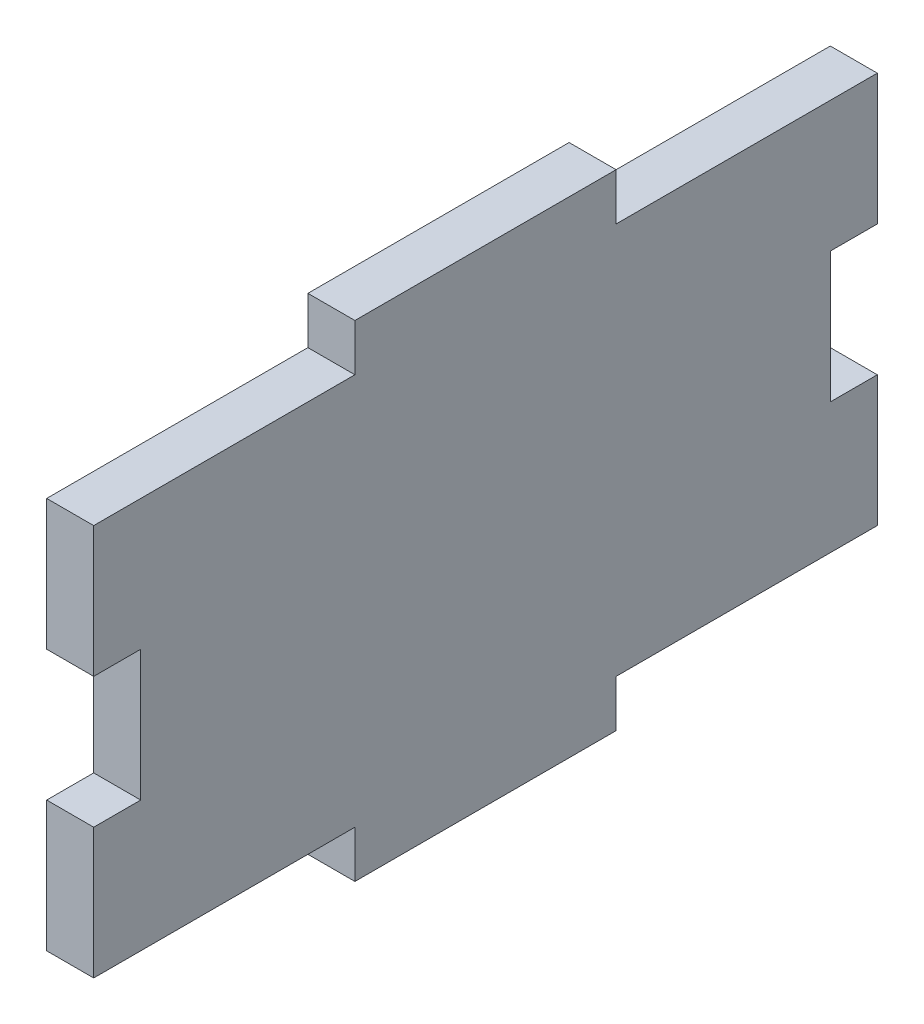
SolidWorks part; units mm, degrees
ref_plane "Front Plane" through (0, 0, 0) normal (0, 0, 1) x (1, 0, 0)
ref_plane "Top Plane" through (0, 0, 0) normal (0, 1, 0) x (1, 0, 0)
ref_plane "Right Plane" through (0, 0, 0) normal (1, 0, 0) x (0, 0, -1)
sketch "Sides" plane through (0, 0, 0) normal (1, 0, 0) x (0, 0, -1)
  line L0 (0, 16.6667) -> (0, 25)
  line L1 (0, 0) -> (16.6667, 0)
  line L2 (0, 0) -> (0, 8.3333)
  line L3 (0, 25) -> (16.6667, 25)
  line L4 (50, 0) -> (50, 8.3333)
  line L5 (0, 16.6667) -> (3, 16.6667)
  line L6 (33.3333, 25) -> (50, 25)
  line L7 (0, 8.3333) -> (3, 8.3333)
  line L8 (3, 16.6667) -> (3, 8.3333)
  line L9 (33.3333, 0) -> (50, 0)
  line L10 (16.6667, 25) -> (16.6667, 28)
  line L11 (16.6667, 28) -> (33.3333, 28)
  line L12 (33.3333, 25) -> (33.3333, 28)
  line L13 (50, 16.6667) -> (50, 25)
  line L14 (33.3333, 0) -> (33.3333, -3)
  line L15 (16.6667, 0) -> (16.6667, -3)
  line L16 (16.6667, -3) -> (33.3333, -3)
  line L17 (50, 16.6667) -> (47, 16.6667)
  line L18 (50, 8.3333) -> (47, 8.3333)
  line L19 (47, 16.6667) -> (47, 8.3333)
  spline B0 degree 3 poles (37.9007, 16.1432) (37.9696, 16.013) (38.0385, 15.9215) (38.0688, 15.8186) (38.1861, 15.4206) (38.4536, 15.3089) (38.8343, 15.3923) knots 92 92 92 92 93 93 93 94 94 94 94
  spline B1 degree 3 poles (37.6339, 15.6309) (37.6975, 15.7979) (37.7985, 15.9506) (37.9007, 16.1432) knots 91 91 91 91 92 92 92 92
  spline B2 degree 3 poles (37.0018, 15.3964) (37.0947, 15.3917) (37.1566, 15.3946) (37.2162, 15.3844) (37.4268, 15.3485) (37.5558, 15.4258) (37.6339, 15.6309) knots 89 89 89 89 90 90 90 91 91 91 91
  spline B3 degree 3 poles (37.5757, 16.3534) (37.383, 16.0453) (37.201, 15.7305) (37.0018, 15.3964) knots 88 88 88 88 89 89 89 89
  spline B4 degree 3 poles (37.0621, 17.5139) (37.249, 17.1881) (37.4076, 16.899) (37.58, 16.6183) (37.641, 16.5188) (37.6357, 16.4493) (37.5757, 16.3534) knots 86 86 86 86 87 87 87 88 88 88 88
  spline B5 degree 3 poles (37.9359, 16.8363) (37.8282, 17.0413) (37.7407, 17.2159) (37.6448, 17.3857) (37.6168, 17.4354) (37.5683, 17.5029) (37.5231, 17.508) (37.3821, 17.5239) (37.2381, 17.5139) (37.0621, 17.5139) knots 83 83 83 83 84 84 84 85 85 85 86 86 86 86
  spline B6 degree 3 poles (38.769, 17.5) (38.3221, 17.5403) (38.3228, 17.5399) (38.144, 17.2062) (38.0821, 17.0907) (38.0156, 16.9777) (37.9359, 16.8363) knots 81 81 81 81 82 82 82 83 83 83 83
  spline B7 degree 3 poles (38.2937, 16.7248) (38.4611, 16.9705) (38.6061, 17.2315) (38.769, 17.5) knots 80 80 80 80 81 81 81 81
  spline B8 degree 3 poles (38.8343, 15.4346) (38.6548, 15.727) (38.4833, 16.0248) (38.2925, 16.3097) (38.1922, 16.4593) (38.1918, 16.5754) (38.2937, 16.7248) knots 78 78 78 78 79 79 79 80 80 80 80
  spline B9 degree 3 poles (30.8757, 15.4021) (30.8757, 16.4401) (30.8757, 17.4613) (30.8757, 18.4826) knots 75 75 75 75 76 76 76 76
  spline B10 degree 3 poles (30.3889, 15.4021) (30.5643, 15.4021) (30.7145, 15.4021) (30.8757, 15.4021) knots 74 74 74 74 75 75 75 75
  spline B11 degree 3 poles (30.3677, 18.4826) (30.3747, 18.3992) (30.3878, 18.3157) (30.388, 18.2322) (30.3895, 17.3723) (30.3889, 16.5124) (30.3889, 15.6525) (30.3889, 15.5696) (30.3889, 15.4866) (30.3889, 15.4021) knots 71 71 71 71 72 72 72 73 73 73 74 74 74 74
  spline B12 degree 3 poles (28.096, 16.4603) (28.054, 15.8765) (28.3772, 15.4167) (28.8864, 15.3623) (29.1265, 15.3367) (29.3757, 15.3811) (29.6191, 15.408) (29.7791, 15.4258) (29.8461, 15.5147) (29.8435, 15.695) (29.8318, 16.4913) (29.8375, 17.2878) (29.8394, 18.0842) (29.8397, 18.2171) (29.8526, 18.3498) (29.8597, 18.4826) knots 65 65 65 65 66 66 66 67 67 67 68 68 68 69 69 69 70 70 70 70
  spline B13 degree 3 poles (29.3517, 17.5081) (29.257, 17.5202) (29.1877, 17.531) (29.1181, 17.5378) (28.7241, 17.5763) (28.3632, 17.3793) (28.2162, 17.0132) (28.1467, 16.8403) (28.1095, 16.6471) (28.096, 16.4603) knots 62 62 62 62 63 63 63 64 64 64 65 65 65 65
  spline B14 degree 3 poles (29.3517, 18.4826) (29.3517, 18.161) (29.3517, 17.8393) (29.3517, 17.5081) knots 61 61 61 61 62 62 62 62
  spline B15 degree 3 poles (25.9347, 16.5772) (25.8666, 15.9569) (26.1383, 15.4619) (26.6498, 15.3831) (26.9323, 15.3396) (27.2337, 15.4011) (27.5236, 15.4381) (27.5779, 15.4451) (27.6586, 15.5601) (27.659, 15.6256) (27.6656, 16.5779) (27.6606, 17.5303) (27.6583, 18.4826) knots 56 56 56 56 57 57 57 58 58 58 59 59 59 60 60 60 60
  spline B16 degree 3 poles (27.1927, 17.52) (26.3737, 17.5636) (26.0122, 17.2835) (25.9347, 16.5772) knots 55 55 55 55 56 56 56 56
  spline B17 degree 3 poles (27.1927, 18.4826) (27.1927, 18.1622) (27.1927, 17.8417) (27.1927, 17.52) knots 54 54 54 54 55 55 55 55
  spline B18 degree 3 poles (11.233, 15.096) (11.2467, 15.0359) (11.269, 14.9763) (11.2729, 14.9156) (11.3305, 14.0247) (11.4934, 13.1538) (11.7919, 12.3125) (12.513, 10.2803) (13.786, 8.7195) (15.7277, 7.7333) (15.8924, 7.6496) (16.0298, 7.6431) (16.2023, 7.7264) (17.0715, 8.1463) (17.8261, 8.7177) (18.4733, 9.4283) (19.9556, 11.0557) (20.6136, 13.013) (20.707, 15.1763) (20.7463, 16.0843) (20.7081, 16.9955) (20.7117, 17.9052) (20.7124, 18.0633) (20.6658, 18.1267) (20.4986, 18.1382) (19.3034, 18.2204) (18.1088, 18.3108) (16.9143, 18.4026) (16.6849, 18.4202) (16.4569, 18.4555) (16.2283, 18.4826) knots 43 43 43 43 44 44 44 45 45 45 46 46 46 47 47 47 48 48 48 49 49 49 50 50 50 51 51 51 52 52 52 53 53 53 53
  spline B19 degree 3 poles (21.9433, 10.336) (21.9433, 9.4175) (21.9433, 8.5102) (21.9433, 7.603) knots 40 40 40 40 41 41 41 41
  spline B20 degree 3 poles (22.2955, 10.336) (22.1664, 10.336) (22.0634, 10.336) (21.9433, 10.336) knots 39 39 39 39 40 40 40 40
  spline B21 degree 3 poles (22.2955, 7.8871) (22.2955, 8.7206) (22.2955, 9.5273) (22.2955, 10.336) knots 38 38 38 38 39 39 39 39
  spline B22 degree 3 poles (23.1295, 7.8871) (22.834, 7.8871) (22.5772, 7.8871) (22.2955, 7.8871) knots 37 37 37 37 38 38 38 38
  spline B23 degree 3 poles (23.0863, 7.603) (23.0991, 7.6872) (23.1119, 7.7714) (23.1295, 7.8871) knots 36 36 36 36 37 37 37 37
  spline B24 degree 3 poles (24.4833, 7.603) (24.7207, 7.7061) (24.8945, 7.8732) (24.9746, 8.1216) (25.0992, 8.5081) (25.1024, 8.898) (24.9668, 9.2823) (24.8503, 9.6123) (24.5913, 9.7938) (24.2469, 9.8032) (23.9056, 9.8126) (23.6328, 9.6421) (23.5054, 9.3162) (23.4498, 9.1739) (23.4151, 9.0194) (23.397, 8.8673) (23.3247, 8.259) (23.5198, 7.8422) (23.9753, 7.603) knots 29 29 29 29 30 30 30 31 31 31 32 32 32 33 33 33 34 34 34 35 35 35 35
  spline B25 degree 3 poles (27.0657, 7.603) (27.0685, 8.1439) (27.0827, 8.685) (27.0699, 9.2256) (27.0627, 9.5265) (26.8976, 9.7311) (26.5979, 9.7563) (26.2895, 9.7822) (25.9735, 9.7341) (25.6629, 9.699) (25.6143, 9.6935) (25.5412, 9.5853) (25.5405, 9.524) (25.5337, 8.8837) (25.5394, 8.2433) (25.5417, 7.603) knots 23 23 23 23 24 24 24 25 25 25 26 26 26 27 27 27 28 28 28 28
  spline B26 degree 3 poles (28.7964, 9.7546) (28.7149, 9.7608) (28.6589, 9.7641) (28.6031, 9.7694) (28.094, 9.8181) (27.7454, 9.5822) (27.6049, 9.0939) (27.4189, 8.4471) (27.6038, 7.9561) (28.1663, 7.603) knots 19 19 19 19 20 20 20 21 21 21 22 22 22 22
  spline B27 degree 3 poles (28.7964, 10.7255) (28.7964, 10.3977) (28.7964, 10.0791) (28.7964, 9.7546) knots 18 18 18 18 19 19 19 19
  spline B28 degree 3 poles (29.1611, 10.7255) (29.0272, 10.7255) (28.9243, 10.7255) (28.7964, 10.7255) knots 17 17 17 17 18 18 18 18
  spline B29 degree 3 poles (28.886, 7.603) (29.139, 7.6639) (29.1717, 7.8345) (29.1671, 8.0707) (29.1515, 8.8802) (29.1611, 9.6903) (29.1611, 10.5001) (29.1611, 10.5745) (29.1611, 10.6489) (29.1611, 10.7255) knots 14 14 14 14 15 15 15 16 16 16 17 17 17 17
  spline B30 degree 3 poles (30.7487, 7.603) (30.8756, 7.7184) (31.0467, 7.8108) (31.1215, 7.9536) (31.3785, 8.4443) (31.3837, 8.9613) (31.1172, 9.448) (30.8695, 9.9003) (30.1799, 9.9281) (29.8562, 9.5235) (29.4217, 8.9804) (29.605, 7.9513) (30.1983, 7.603) knots 9 9 9 9 10 10 10 11 11 11 12 12 12 13 13 13 13
  spline B31 degree 3 poles (33.3129, 9.2242) (33.301, 9.5315) (33.1224, 9.7344) (32.8143, 9.7619) (32.5257, 9.7877) (32.2298, 9.7413) (31.938, 9.7162) (31.8082, 9.705) (31.7593, 9.6258) (31.7612, 9.4851) (31.7695, 8.8578) (31.7647, 8.2304) (31.7647, 7.603) knots 4 4 4 4 5 5 5 6 6 6 7 7 7 8 8 8 8
  spline B32 degree 3 poles (33.2887, 7.603) (33.2994, 7.6288) (33.3194, 7.6546) (33.3194, 7.6805) (33.3204, 8.1951) (33.333, 8.7103) (33.3129, 9.2242) knots 2 2 2 2 3 3 3 4 4 4 4
  spline B33 degree 3 poles (22.2241, 15.3979) (22.2888, 16.0502) (22.3524, 16.6915) (22.4159, 17.3328) knots 15 15 15 15 16 16 16 16
  spline B34 degree 3 poles (21.7959, 15.3979) (21.9515, 15.3979) (22.0815, 15.3979) (22.2241, 15.3979) knots 14 14 14 14 15 15 15 15
  spline B35 degree 3 poles (22.0962, 18.093) (21.9961, 17.1939) (21.8966, 16.3011) (21.7959, 15.3979) knots 13 13 13 13 14 14 14 14
  spline B36 degree 3 poles (22.6144, 18.093) (22.4361, 18.093) (22.2756, 18.093) (22.0962, 18.093) knots 12 12 12 12 13 13 13 13
  spline B37 degree 3 poles (23.1658, 16.1257) (22.9701, 16.8241) (22.792, 17.4594) (22.6144, 18.093) knots 11 11 11 11 12 12 12 12
  spline B38 degree 3 poles (23.7366, 18.0939) (23.5509, 17.4535) (23.3663, 16.8172) (23.1658, 16.1257) knots 10 10 10 10 11 11 11 11
  spline B39 degree 3 poles (24.2541, 18.0939) (24.0681, 18.0939) (23.9072, 18.0939) (23.7366, 18.0939) knots 9 9 9 9 10 10 10 10
  spline B40 degree 3 poles (24.5558, 15.3989) (24.4542, 16.3064) (24.3543, 17.1992) (24.2541, 18.0939) knots 8 8 8 8 9 9 9 9
  spline B41 degree 3 poles (24.0748, 15.3989) (24.241, 15.3989) (24.392, 15.3989) (24.5558, 15.3989) knots 7 7 7 7 8 8 8 8
  spline B42 degree 3 poles (23.8838, 17.3298) (23.9472, 16.6888) (24.0106, 16.0478) (24.0748, 15.3989) knots 6 6 6 6 7 7 7 7
  spline B43 degree 3 poles (23.8593, 17.3332) (23.8675, 17.3321) (23.8756, 17.3309) (23.8838, 17.3298) knots 5 5 5 5 6 6 6 6
  spline B44 degree 3 poles (22.4414, 17.3366) (22.6091, 16.75) (22.7792, 16.1642) (22.9426, 15.5765) (22.9754, 15.4584) (23.002, 15.3768) (23.1581, 15.3793) (23.3096, 15.3817) (23.3227, 15.4711) (23.3523, 15.5748) (23.5197, 16.1614) (23.69, 16.7472) (23.8593, 17.3332) knots 1 1 1 1 2 2 2 3 3 3 4 4 4 5 5 5 5
  spline B45 degree 3 poles (22.4159, 17.3328) (22.4244, 17.334) (22.4329, 17.3353) (22.4414, 17.3366) knots 0 0 0 0 1 1 1 1
  spline B46 degree 3 poles (21.9024, 14.2791) (21.9024, 13.5852) (21.8849, 12.9029) (21.9092, 12.2221) (21.923, 11.8339) (22.2793, 11.5513) (22.692, 11.5336) (23.2176, 11.5111) (23.5793, 11.7377) (23.6706, 12.1478) (23.6782, 12.182) (23.6831, 12.2176) (23.6832, 12.2525) (23.6839, 12.9214) (23.6837, 13.5903) (23.6837, 14.279) knots 9 9 9 9 10 10 10 11 11 11 12 12 12 13 13 13 14 14 14 14
  spline B47 degree 3 poles (22.4018, 14.2791) (22.2163, 14.2791) (22.064, 14.2791) (21.9024, 14.2791) knots 8 8 8 8 9 9 9 9
  spline B48 degree 3 poles (23.2135, 14.279) (23.2135, 14.1906) (23.2135, 14.1145) (23.2135, 14.0384) (23.2135, 13.4749) (23.2165, 12.9113) (23.212, 12.3478) (23.21, 12.0973) (23.0566, 11.9332) (22.8335, 11.9222) (22.6031, 11.9109) (22.4314, 12.0726) (22.4088, 12.3259) (22.402, 12.4029) (22.4022, 12.4807) (22.4021, 12.5582) (22.4016, 13.0583) (22.4018, 13.5585) (22.4018, 14.0587) (22.4018, 14.1328) (22.4018, 14.207) (22.4018, 14.2791) knots 1 1 1 1 2 2 2 3 3 3 4 4 4 5 5 5 6 6 6 7 7 7 8 8 8 8
  spline B49 degree 3 poles (23.6837, 14.279) (23.5167, 14.279) (23.3731, 14.279) (23.2135, 14.279) knots 0 0 0 0 1 1 1 1
  spline B50 degree 3 poles (25.4148, 11.5831) (25.5892, 11.5831) (25.7291, 11.5831) (25.8952, 11.5831) knots 14 14 14 14 15 15 15 15
  spline B51 degree 3 poles (24.7161, 11.5845) (24.7161, 11.6689) (24.7161, 11.7448) (24.7161, 11.8206) (24.7161, 12.2784) (24.7141, 12.7363) (24.7185, 13.194) (24.7192, 13.2587) (24.7452, 13.3763) (24.7694, 13.379) (24.9258, 13.3961) (25.0982, 13.425) (25.2382, 13.3746) (25.3224, 13.3444) (25.4021, 13.1796) (25.4068, 13.0719) (25.4259, 12.6431) (25.4148, 12.213) (25.4148, 11.7834) (25.4148, 11.7169) (25.4148, 11.6504) (25.4148, 11.5831) knots 7 7 7 7 8 8 8 9 9 9 10 10 10 11 11 11 12 12 12 13 13 13 14 14 14 14
  spline B52 degree 3 poles (24.2225, 11.5845) (24.3987, 11.5845) (24.5446, 11.5845) (24.7161, 11.5845) knots 6 6 6 6 7 7 7 7
  spline B53 degree 3 poles (25.8952, 11.5831) (25.8952, 12.139) (25.9083, 12.6736) (25.8897, 13.2071) (25.8802, 13.4782) (25.6847, 13.6331) (25.4329, 13.6963) (25.0687, 13.7878) (24.7043, 13.7559) (24.352, 13.6371) (24.2934, 13.6173) (24.2299, 13.5089) (24.2282, 13.4399) (24.2171, 12.9965) (24.2225, 12.5526) (24.2225, 12.1089) (24.2225, 11.9357) (24.2225, 11.7625) (24.2225, 11.5845) knots 0 0 0 0 1 1 1 2 2 2 3 3 3 4 4 4 5 5 5 6 6 6 6
  spline B54 degree 3 poles (37.3169, 11.738) (37.3471, 11.6406) (37.3406, 11.5165) (37.3087, 11.4184) (37.2356, 11.1935) (37.1364, 10.9771) (37.0405, 10.7392) knots 10 10 10 10 11 11 11 12 12 12 12
  spline B55 degree 3 poles (36.7512, 13.4834) (36.9411, 12.902) (37.1361, 12.3222) (37.3169, 11.738) knots 9 9 9 9 10 10 10 10
  spline B56 degree 3 poles (36.6907, 13.6788) (36.7101, 13.6159) (36.7297, 13.5493) (36.7512, 13.4834) knots 8 8 8 8 9 9 9 9
  spline B57 degree 3 poles (37.6172, 12.1517) (37.5052, 12.5694) (37.4072, 12.9339) (37.3099, 13.2986) (37.1897, 13.749) (37.19, 13.7491) (36.7178, 13.6951) (36.7119, 13.6944) (36.7066, 13.6886) (36.6907, 13.6788) knots 5 5 5 5 6 6 6 7 7 7 8 8 8 8
  spline B58 degree 3 poles (37.979, 13.4368) (37.8859, 13.0221) (37.7508, 12.6168) (37.6172, 12.1517) knots 4 4 4 4 5 5 5 5
  spline B59 degree 3 poles (38.5225, 13.6954) (38.4473, 13.7) (38.3985, 13.6985) (38.3512, 13.7065) (38.1335, 13.7439) (38.0303, 13.6656) (37.979, 13.4368) knots 2 2 2 2 3 3 3 4 4 4 4
  spline B60 degree 3 poles (37.5584, 10.7392) (37.8783, 11.7202) (38.1978, 12.6999) (38.5225, 13.6954) knots 1 1 1 1 2 2 2 2
  spline B61 degree 3 poles (37.0405, 10.7392) (37.2271, 10.7392) (37.3865, 10.7392) (37.5584, 10.7392) knots 0 0 0 0 1 1 1 1
  spline B62 degree 3 poles (31.8282, 16.2724) (32.2356, 16.3332) (32.6454, 16.3943) (33.0542, 16.4553) knots 6 6 6 6 7 7 7 7
  spline B63 degree 3 poles (32.9017, 15.793) (32.1812, 15.574) (31.7603, 15.7636) (31.8282, 16.2724) knots 5 5 5 5 6 6 6 6
  spline B64 degree 3 poles (33.0092, 15.5097) (32.9739, 15.6027) (32.9376, 15.6984) (32.9017, 15.793) knots 4 4 4 4 5 5 5 5
  spline B65 degree 3 poles (33.0542, 16.4553) (33.1669, 16.946) (32.915, 17.4176) (32.483, 17.5281) (31.9716, 17.6589) (31.5208, 17.4127) (31.3836, 16.9077) (31.3364, 16.7343) (31.318, 16.5462) (31.3244, 16.3661) (31.3565, 15.4732) (32.2194, 15.03) (33.0092, 15.5097) knots 0 0 0 0 1 1 1 2 2 2 3 3 3 4 4 4 4
  spline B66 degree 3 poles (35.5556, 16.2705) (35.9713, 16.3323) (36.3887, 16.3944) (36.8673, 16.4655) knots 8 8 8 8 9 9 9 9
  spline B67 degree 3 poles (36.6521, 15.7797) (35.8376, 15.6235) (35.5473, 15.753) (35.5556, 16.2705) knots 7 7 7 7 8 8 8 8
  spline B68 degree 3 poles (36.7622, 15.492) (36.7204, 15.6012) (36.6858, 15.6916) (36.6521, 15.7797) knots 6 6 6 6 7 7 7 7
  spline B69 degree 3 poles (35.5566, 15.4573) (35.9546, 15.2601) (36.3579, 15.3185) (36.7622, 15.492) knots 5 5 5 5 6 6 6 6
  spline B70 degree 3 poles (35.1112, 16.8593) (35.0758, 16.7034) (35.0663, 16.5383) (35.0689, 16.3777) (35.0751, 15.9912) (35.1852, 15.6414) (35.5566, 15.4573) knots 3 3 3 3 4 4 4 5 5 5 5
  spline B71 degree 3 poles (36.8673, 16.4655) (36.8156, 16.6967) (36.7869, 16.9121) (36.7173, 17.1134) (36.6386, 17.341) (36.455, 17.4719) (36.2201, 17.5299) (35.6898, 17.6609) (35.2318, 17.3904) (35.1112, 16.8593) knots 0 0 0 0 1 1 1 2 2 2 3 3 3 3
  spline B72 degree 3 poles (29.8012, 12.4588) (30.2156, 12.5207) (30.6318, 12.5829) (31.0685, 12.6481) knots 7 7 7 7 8 8 8 8
  spline B73 degree 3 poles (30.8895, 11.9721) (30.1156, 11.7889) (29.7539, 11.9532) (29.8012, 12.4588) knots 6 6 6 6 7 7 7 7
  spline B74 degree 3 poles (30.9881, 11.7063) (30.9552, 11.795) (30.9218, 11.885) (30.8895, 11.9721) knots 5 5 5 5 6 6 6 6
  spline B75 degree 3 poles (29.3896, 13.1559) (29.3197, 12.8784) (29.2969, 12.565) (29.3488, 12.2854) (29.4807, 11.5741) (30.3929, 11.264) (30.9881, 11.7063) knots 3 3 3 3 4 4 4 5 5 5 5
  spline B76 degree 3 poles (31.0685, 12.6481) (31.0611, 12.7701) (31.0602, 12.8815) (31.0465, 12.9914) (30.9919, 13.427) (30.7329, 13.6996) (30.3422, 13.7387) (29.8722, 13.7857) (29.4979, 13.5855) (29.3896, 13.1559) knots 0 0 0 0 1 1 1 2 2 2 3 3 3 3
  spline B77 degree 3 poles (27.7844, 13.6967) (27.6138, 13.6967) (27.4537, 13.6967) (27.2614, 13.6967) knots 9 9 9 9 10 10 10 10
  spline B78 degree 3 poles (28.1875, 12.2323) (28.0537, 12.7185) (27.9198, 13.2047) (27.7844, 13.6967) knots 8 8 8 8 9 9 9 9
  spline B79 degree 3 poles (28.2301, 12.2267) (28.2159, 12.2286) (28.2017, 12.2304) (28.1875, 12.2323) knots 7 7 7 7 8 8 8 8
  spline B80 degree 3 poles (28.6441, 13.6943) (28.5043, 13.1987) (28.3672, 12.7127) (28.2301, 12.2267) knots 6 6 6 6 7 7 7 7
  spline B81 degree 3 poles (29.1036, 13.6943) (28.9376, 13.6943) (28.7926, 13.6943) (28.6441, 13.6943) knots 5 5 5 5 6 6 6 6
  spline B82 degree 3 poles (27.2614, 13.6967) (27.4876, 13.0001) (27.7035, 12.3318) (27.9244, 11.6652) (27.9365, 11.6287) (27.9861, 11.5887) (28.0251, 11.5797) (28.3186, 11.5115) (28.4232, 11.5737) (28.5125, 11.8573) (28.5294, 11.9109) (28.5492, 11.9636) (28.5664, 12.0172) (28.7442, 12.5719) (28.9218, 13.1266) (29.1036, 13.6943) knots 0 0 0 0 1 1 1 2 2 2 3 3 3 4 4 4 5 5 5 5
  spline B83 degree 3 poles (35.3954, 13.4015) (35.4715, 13.3874) (35.5382, 13.375) (35.6187, 13.3601) knots 13 13 13 13 14 14 14 14
  spline B84 degree 3 poles (35.3954, 13.6882) (35.3954, 13.5863) (35.3954, 13.4973) (35.3954, 13.4015) knots 12 12 12 12 13 13 13 13
  spline B85 degree 3 poles (35.5961, 13.7188) (35.5309, 13.7089) (35.4646, 13.6988) (35.3954, 13.6882) knots 11 11 11 11 12 12 12 12
  spline B86 degree 3 poles (36.1151, 14.3146) (35.9436, 14.2625) (35.7497, 14.2597) (35.6658, 14.1622) (35.5842, 14.0673) (35.6153, 13.8755) (35.5961, 13.7188) knots 9 9 9 9 10 10 10 11 11 11 11
  spline B87 degree 3 poles (36.1151, 13.7177) (36.1151, 13.9172) (36.1151, 14.0981) (36.1151, 14.3146) knots 8 8 8 8 9 9 9 9
  spline B88 degree 3 poles (36.4508, 13.6975) (36.3365, 13.7044) (36.2343, 13.7105) (36.1151, 13.7177) knots 7 7 7 7 8 8 8 8
  spline B89 degree 3 poles (36.4508, 13.3957) (36.4508, 13.5005) (36.4508, 13.5956) (36.4508, 13.6975) knots 6 6 6 6 7 7 7 7
  spline B90 degree 3 poles (36.1227, 13.3664) (36.2424, 13.3771) (36.3454, 13.3863) (36.4508, 13.3957) knots 5 5 5 5 6 6 6 6
  spline B91 degree 3 poles (36.1269, 12.0736) (36.1136, 12.5017) (36.1227, 12.9305) (36.1227, 13.3664) knots 4 4 4 4 5 5 5 5
  spline B92 degree 3 poles (36.4524, 11.8814) (36.2912, 11.8719) (36.1328, 11.8845) (36.1269, 12.0736) knots 3 3 3 3 4 4 4 4
  spline B93 degree 3 poles (36.4524, 11.6094) (36.4524, 11.6998) (36.4524, 11.7892) (36.4524, 11.8814) knots 2 2 2 2 3 3 3 3
  spline B94 degree 3 poles (35.6187, 13.3601) (35.6187, 12.939) (35.6079, 12.5233) (35.6216, 12.1084) (35.6367, 11.646) (36.0335, 11.4155) (36.4524, 11.6094) knots 0 0 0 0 1 1 1 2 2 2 2
  spline B95 degree 3 poles (33.4909, 15.7892) (33.4531, 15.6994) (33.4153, 15.6096) (33.3706, 15.5031) knots 15 15 15 15 16 16 16 16
  spline B96 degree 3 poles (34.2083, 15.9048) (34.1601, 15.7383) (34.0184, 15.6804) (33.8579, 15.6991) (33.7367, 15.7132) (33.6188, 15.7567) (33.4909, 15.7892) knots 13 13 13 13 14 14 14 15 15 15 15
  spline B97 degree 3 poles (34.6622, 17.4042) (34.4059, 17.5624) (34.1466, 17.5947) (33.8786, 17.5224) (33.6142, 17.4511) (33.4654, 17.2654) (33.428, 16.9949) (33.3947, 16.7532) (33.5154, 16.5386) (33.7569, 16.4089) (33.8434, 16.3624) (33.9356, 16.3267) (34.0248, 16.2851) (34.1893, 16.2084) (34.2575, 16.0748) (34.2083, 15.9048) knots 8 8 8 8 9 9 9 10 10 10 11 11 11 12 12 12 13 13 13 13
  spline B98 degree 3 poles (34.5572, 17.1398) (34.5934, 17.231) (34.6262, 17.3137) (34.6622, 17.4042) knots 7 7 7 7 8 8 8 8
  spline B99 degree 3 poles (34.0705, 16.7053) (33.9316, 16.7848) (33.8689, 16.9045) (33.9285, 17.0605) (33.9853, 17.2092) (34.1134, 17.2484) (34.2569, 17.2252) (34.3566, 17.2091) (34.4527, 17.1704) (34.5572, 17.1398) knots 4 4 4 4 5 5 5 6 6 6 7 7 7 7
  spline B100 degree 3 poles (34.7265, 15.9403) (34.7538, 16.2324) (34.6249, 16.4357) (34.317, 16.5857) (34.2349, 16.6257) (34.1496, 16.6601) (34.0705, 16.7053) knots 2 2 2 2 3 3 3 4 4 4 4
  spline B101 degree 3 poles (33.3706, 15.5031) (33.6369, 15.3408) (33.9074, 15.3159) (34.1825, 15.3708) (34.4927, 15.4327) (34.7006, 15.6625) (34.7265, 15.9403) knots 0 0 0 0 1 1 1 2 2 2 2
  spline B102 degree 3 poles (32.7717, 13.21) (32.7313, 12.9322) (32.8372, 12.7299) (33.1027, 12.5887) (33.1893, 12.5426) (33.2817, 12.5078) (33.3706, 12.4659) (33.5289, 12.3913) (33.5815, 12.2591) (33.5408, 12.099) (33.4974, 11.9278) (33.3582, 11.8689) (33.1987, 11.8855) (33.0768, 11.8982) (32.9585, 11.9452) (32.8249, 11.9805) knots 11 11 11 11 12 12 12 13 13 13 14 14 14 15 15 15 16 16 16 16
  spline B103 degree 3 poles (33.9934, 13.5869) (33.7626, 13.7481) (33.5135, 13.7712) (33.2599, 13.7244) (32.9885, 13.6744) (32.81, 13.4733) (32.7717, 13.21) knots 9 9 9 9 10 10 10 11 11 11 11
  spline B104 degree 3 poles (33.892, 13.328) (33.9255, 13.4137) (33.9583, 13.4975) (33.9934, 13.5869) knots 8 8 8 8 9 9 9 9
  spline B105 degree 3 poles (33.2649, 13.2372) (33.3204, 13.3258) (33.4556, 13.3936) (33.5646, 13.4108) (33.6633, 13.4264) (33.7748, 13.3609) (33.892, 13.328) knots 6 6 6 6 7 7 7 8 8 8 8
  spline B106 degree 3 poles (34.0542, 12.1007) (34.0885, 12.4078) (33.9731, 12.6114) (33.676, 12.7629) (33.5822, 12.8107) (33.4818, 12.8469) (33.3918, 12.9007) (33.2634, 12.9775) (33.1847, 13.1094) (33.2649, 13.2372) knots 3 3 3 3 4 4 4 5 5 5 6 6 6 6
  spline B107 degree 3 poles (32.7138, 11.7008) (32.9565, 11.5384) (33.2834, 11.4882) (33.5528, 11.5653) (33.8392, 11.6473) (34.0258, 11.8466) (34.0542, 12.1007) knots 1 1 1 1 2 2 2 3 3 3 3
  spline B108 degree 3 poles (32.8249, 11.9805) (32.7886, 11.8893) (32.7506, 11.7935) (32.7138, 11.7008) knots 0 0 0 0 1 1 1 1
  spline B109 degree 3 poles (32.4417, 13.411) (32.4685, 13.5067) (32.4965, 13.6072) (32.5397, 13.7618) knots 8 8 8 8 9 9 9 9
  spline B110 degree 3 poles (31.9832, 11.5938) (31.9832, 12.0832) (31.9832, 12.5543) (31.9832, 13.0254) (31.9831, 13.4288) (31.9831, 13.4287) (32.3934, 13.3967) (32.4061, 13.3957) (32.4195, 13.4041) (32.4417, 13.411) knots 5 5 5 5 6 6 6 7 7 7 8 8 8 8
  spline B111 degree 3 poles (31.5038, 11.5938) (31.6771, 11.5938) (31.8257, 11.5938) (31.9832, 11.5938) knots 4 4 4 4 5 5 5 5
  spline B112 degree 3 poles (32.5397, 13.7618) (32.262, 13.7357) (32.0181, 13.7163) (31.7751, 13.6888) (31.5714, 13.6658) (31.4733, 13.5664) (31.499, 13.3411) (31.5219, 13.1397) (31.5038, 12.9336) (31.5038, 12.7295) (31.5038, 12.3518) (31.5038, 11.974) (31.5038, 11.5938) knots 0 0 0 0 1 1 1 2 2 2 3 3 3 4 4 4 4
  spline B113 degree 3 poles (25.0126, 15.3942) (25.1724, 15.3942) (25.318, 15.3942) (25.478, 15.3942) knots 3 3 3 3 4 4 4 4
  spline B114 degree 3 poles (25.0126, 17.4988) (25.0126, 16.7887) (25.0126, 16.0958) (25.0126, 15.3942) knots 2 2 2 2 3 3 3 3
  spline B115 degree 3 poles (25.478, 17.4988) (25.3135, 17.4988) (25.1635, 17.4988) (25.0126, 17.4988) knots 1 1 1 1 2 2 2 2
  spline B116 degree 3 poles (25.478, 15.3942) (25.478, 16.1125) (25.478, 16.8054) (25.478, 17.4988) knots 0 0 0 0 1 1 1 1
  spline B117 degree 3 poles (26.9063, 11.5872) (26.9063, 12.2932) (26.9063, 12.9876) (26.9063, 13.6934) knots 3 3 3 3 4 4 4 4
  spline B118 degree 3 poles (26.4413, 11.5872) (26.6046, 11.5872) (26.7501, 11.5872) (26.9063, 11.5872) knots 2 2 2 2 3 3 3 3
  spline B119 degree 3 poles (26.4413, 13.6934) (26.4413, 12.9822) (26.4413, 12.2835) (26.4413, 11.5872) knots 1 1 1 1 2 2 2 2
  spline B120 degree 3 poles (26.9063, 13.6934) (26.7449, 13.6934) (26.5946, 13.6934) (26.4413, 13.6934) knots 0 0 0 0 1 1 1 1
  spline B121 degree 3 poles (34.4924, 11.5881) (34.6545, 11.5881) (34.8056, 11.5881) (34.9691, 11.5881) knots 3 3 3 3 4 4 4 4
  spline B122 degree 3 poles (34.4924, 13.6928) (34.4924, 12.9868) (34.4924, 12.2938) (34.4924, 11.5881) knots 2 2 2 2 3 3 3 3
  spline B123 degree 3 poles (34.9691, 13.6928) (34.805, 13.6928) (34.6539, 13.6928) (34.4924, 13.6928) knots 1 1 1 1 2 2 2 2
  spline B124 degree 3 poles (34.9691, 11.5881) (34.9691, 12.3024) (34.9691, 12.996) (34.9691, 13.6928) knots 0 0 0 0 1 1 1 1
  spline B125 degree 3 poles (35.0002, 14.3103) (34.9898, 14.4732) (34.8846, 14.5365) (34.7369, 14.5474) knots 3 3 3 3 4 4 4 4
  spline B126 degree 3 poles (34.7369, 14.5474) (34.5825, 14.5376) (34.4761, 14.4703) (34.4712, 14.3088) (34.4661, 14.1431) (34.5777, 14.0743) (34.7255, 14.0636) (34.8843, 14.0521) (35.0094, 14.1666) (35.0002, 14.3103) knots 0 0 0 0 1 1 1 2 2 2 3 3 3 3
  spline B127 degree 3 poles (26.4005, 14.3031) (26.411, 14.1444) (26.516, 14.0743) (26.6667, 14.0623) knots 3 3 3 3 4 4 4 4
  spline B128 degree 3 poles (26.9362, 14.2971) (26.9346, 14.4589) (26.8364, 14.5348) (26.6833, 14.5444) (26.5254, 14.5543) (26.3912, 14.4441) (26.4005, 14.3031) knots 1 1 1 1 2 2 2 3 3 3 3
  spline B129 degree 3 poles (26.6667, 14.0623) (26.814, 14.0604) (26.9374, 14.1626) (26.9362, 14.2971) knots 0 0 0 0 1 1 1 1
  spline B130 degree 3 poles (24.9864, 18.113) (24.9873, 17.9411) (25.1017, 17.8871) (25.2384, 17.878) knots 3 3 3 3 4 4 4 4
  spline B131 degree 3 poles (25.2384, 17.878) (25.4085, 17.8857) (25.5144, 17.9605) (25.5112, 18.1224) (25.508, 18.2839) (25.3971, 18.3602) (25.2429, 18.3574) (25.0893, 18.3546) (24.9856, 18.2798) (24.9864, 18.113) knots 0 0 0 0 1 1 1 2 2 2 3 3 3 3
  spline B132 degree 3 poles (15.6357, 18.4826) (15.8332, 18.4826) (16.0308, 18.4826) (16.2283, 18.4826) knots 14 14 14 14 15 15 15 15
  spline B133 degree 3 poles (11.2919, 18.1328) (12.47, 18.2206) (13.6361, 18.3057) (14.8018, 18.3954) (15.0803, 18.4168) (15.3577, 18.4531) (15.6357, 18.4826) knots 12 12 12 12 13 13 13 14 14 14 14
  spline B134 degree 3 poles (11.233, 17.6783) (11.2523, 17.8275) (11.2717, 17.9767) (11.2919, 18.1328) knots 11 11 11 11 12 12 12 12
  spline B135 degree 3 poles (11.233, 15.096) (11.233, 15.9567) (11.233, 16.8175) (11.233, 17.6783) knots 10 10 10 10 11 11 11 11
  spline B136 degree 3 poles (16.2283, 18.4826) (16.4569, 18.4555) (16.6849, 18.4202) (16.9143, 18.4026) (18.1088, 18.3108) (19.3034, 18.2204) (20.4986, 18.1382) (20.6658, 18.1267) (20.7124, 18.0633) (20.7117, 17.9052) (20.7081, 16.9955) (20.7463, 16.0843) (20.707, 15.1763) (20.6136, 13.013) (19.9556, 11.0557) (18.4733, 9.4283) (17.8261, 8.7177) (17.0715, 8.1463) (16.2023, 7.7264) (16.0298, 7.6431) (15.8924, 7.6496) (15.7277, 7.7333) (13.786, 8.7195) (12.513, 10.2803) (11.7919, 12.3125) (11.4934, 13.1538) (11.3305, 14.0247) (11.2729, 14.9156) (11.269, 14.9763) (11.2467, 15.0359) (11.233, 15.096) knots 0 0 0 0 1 1 1 2 2 2 3 3 3 4 4 4 5 5 5 6 6 6 7 7 7 8 8 8 9 9 9 10 10 10 10
  spline B137 degree 3 poles (19.3619, 12.7625) (19.2958, 12.9159) (19.2736, 13.0544) (19.1936, 13.1368) (18.9656, 13.3715) (18.7422, 13.6306) (18.4663, 13.7954) (17.699, 14.2539) (16.8372, 14.3576) (15.9602, 14.3443) (15.2977, 14.3343) (14.667, 14.1588) (13.9907, 13.9032) knots 24 24 24 24 25 25 25 26 26 26 27 27 27 28 28 28 28
  spline B138 degree 3 poles (14.3345, 13.4321) (15.085, 13.6323) (15.876, 13.6643) (16.6666, 13.4317) (16.8074, 13.3903) (16.9052, 13.3768) (17.0118, 13.505) (17.1096, 13.6225) (17.2562, 13.6862) (17.4106, 13.6049) (17.5718, 13.52) (17.619, 13.353) (17.5615, 13.2043) (17.4809, 12.9962) (17.6014, 12.9058) (17.7268, 12.803) (17.7521, 12.7822) (17.7889, 12.7644) (17.8204, 12.7642) (18.3181, 12.7618) (18.8158, 12.7625) (19.3619, 12.7625) knots 17 17 17 17 18 18 18 19 19 19 20 20 20 21 21 21 22 22 22 23 23 23 24 24 24 24
  spline B139 degree 3 poles (14.0473, 13.2182) (14.004, 13.163) (13.9532, 13.1121) (13.9195, 13.0516) (13.8883, 12.9954) (13.8461, 12.919) (13.8629, 12.8702) (13.8794, 12.8222) (13.9752, 12.7593) (14.0165, 12.7712) (14.0965, 12.7943) (14.2011, 12.851) (14.2265, 12.9194) (14.2831, 13.0713) (14.297, 13.2391) (14.3345, 13.4321) knots 12 12 12 12 13 13 13 14 14 14 15 15 15 16 16 16 17 17 17 17
  spline B140 degree 3 poles (14.0025, 13.2749) (14.0175, 13.256) (14.0324, 13.2371) (14.0473, 13.2182) knots 11 11 11 11 12 12 12 12
  spline B141 degree 3 poles (13.9907, 13.9032) (14.0379, 14.0165) (14.0757, 14.082) (14.0919, 14.1526) (14.1109, 14.2353) (14.1499, 14.3553) (14.1114, 14.4009) (14.0259, 14.5021) (13.9009, 14.4531) (13.849, 14.3511) (13.791, 14.2371) (13.7548, 14.1025) (13.7477, 13.9748) (13.7405, 13.8441) (13.7184, 13.7591) (13.5727, 13.7456) (13.5332, 13.7419) (13.4948, 13.7197) (13.4574, 13.7028) (13.2237, 13.5967) (12.9934, 13.4823) (12.756, 13.3855) (12.5821, 13.3145) (12.5959, 13.1813) (12.6348, 13.0526) (12.6743, 12.9216) (12.7733, 12.8234) (12.9231, 12.88) (13.1424, 12.9628) (13.3503, 13.0755) (13.5692, 13.1596) (13.7079, 13.2129) (13.8577, 13.2374) (14.0025, 13.2749) knots 0 0 0 0 1 1 1 2 2 2 3 3 3 4 4 4 5 5 5 6 6 6 7 7 7 8 8 8 9 9 9 10 10 10 11 11 11 11
  spline B142 degree 3 poles (14.3874, 11.2955) (14.3729, 11.2619) (14.3689, 11.2483) (14.3617, 11.2367) (14.322, 11.1714) (14.2721, 11.1097) (14.2483, 11.0392) (14.2427, 11.0226) (14.3394, 10.9408) (14.3633, 10.9507) (14.4416, 10.9833) (14.5384, 11.0295) (14.572, 11.098) (14.6222, 11.2002) (14.6247, 11.3258) (14.6513, 11.4607) knots 20 20 20 20 21 21 21 22 22 22 23 23 23 24 24 24 25 25 25 25
  spline B143 degree 3 poles (14.4609, 12.3106) (14.3873, 12.294) (14.2803, 12.3013) (14.2475, 12.2555) (14.1906, 12.1762) (14.1591, 12.0648) (14.1546, 11.9652) (14.1493, 11.8454) (14.1268, 11.7799) (14, 11.7322) (13.7545, 11.64) (13.5169, 11.5242) (13.2831, 11.4043) (13.1589, 11.3406) (13.1478, 11.2089) (13.2279, 11.1154) (13.2824, 11.0518) (13.4116, 10.9904) (13.4807, 11.0123) (13.7456, 11.0961) (13.9988, 11.2163) (14.259, 11.3164) (14.2926, 11.3293) (14.341, 11.304) (14.3874, 11.2955) knots 12 12 12 12 13 13 13 14 14 14 15 15 15 16 16 16 17 17 17 18 18 18 19 19 19 20 20 20 20
  spline B144 degree 3 poles (14.3692, 11.9007) (14.4164, 11.9934) (14.4555, 12.0413) (14.4641, 12.0941) (14.4754, 12.1643) (14.4631, 12.2383) (14.4609, 12.3106) knots 10 10 10 10 11 11 11 12 12 12 12
  spline B145 degree 3 poles (18.7415, 10.9495) (18.6232, 11.1449) (18.5633, 11.3116) (18.448, 11.419) (18.26, 11.5943) (18.0539, 11.7698) (17.8237, 11.8768) (17.0479, 12.2376) (16.2279, 12.3197) (15.389, 12.1582) (15.0626, 12.0954) (14.7431, 11.9964) (14.3692, 11.9007) knots 6 6 6 6 7 7 7 8 8 8 9 9 9 10 10 10 10
  spline B146 degree 3 poles (14.6513, 11.4607) (15.2238, 11.613) (15.8121, 11.6777) (16.407, 11.5133) (16.5224, 11.4813) (16.5984, 11.4871) (16.6826, 11.5835) (16.786, 11.702) (16.9485, 11.7771) (17.0744, 11.6681) (17.1616, 11.5926) (17.2023, 11.4309) (17.2101, 11.3044) (17.2196, 11.1491) (17.3022, 10.9605) (17.4564, 10.9547) (17.8604, 10.9393) (18.2655, 10.9495) (18.7415, 10.9495) knots 0 0 0 0 1 1 1 2 2 2 3 3 3 4 4 4 5 5 5 6 6 6 6
  spline B147 degree 3 poles (14.4719, 16.7815) (14.6537, 16.7581) (14.699, 16.6132) (14.7271, 16.4535) (14.76, 16.2663) (14.8032, 16.0805) (14.8276, 15.8923) (14.852, 15.7043) (14.9443, 15.5771) (15.1205, 15.5152) (15.6856, 15.3168) (16.2527, 15.3173) (16.8177, 15.514) (16.9829, 15.5716) (17.0804, 15.6877) (17.1031, 15.8713) (17.1273, 16.0666) (17.1727, 16.2592) (17.2059, 16.4535) (17.2334, 16.6147) (17.2819, 16.7568) (17.472, 16.7809) knots 20 20 20 20 21 21 21 22 22 22 23 23 23 24 24 24 25 25 25 26 26 26 27 27 27 27
  spline B148 degree 3 poles (15.1104, 16.4729) (15.0469, 16.6023) (14.9066, 16.7538) (14.9358, 16.858) (14.9877, 17.0437) (14.866, 17.1182) (14.7912, 17.21) (14.7482, 17.2627) (14.6002, 17.2844) (14.537, 17.2504) (14.4738, 17.2164) (14.4399, 17.0984) (14.4257, 17.0118) (14.4145, 16.9435) (14.4527, 16.8671) (14.4719, 16.7815) knots 15 15 15 15 16 16 16 17 17 17 18 18 18 19 19 19 20 20 20 20
  spline B149 degree 3 poles (15.6926, 17.2446) (15.8074, 17.1082) (15.8381, 16.7202) (15.7393, 16.5942) (15.7207, 16.5706) (15.6813, 16.5564) (15.6493, 16.5513) (15.4777, 16.5239) (15.3054, 16.5008) (15.1104, 16.4729) knots 12 12 12 12 13 13 13 14 14 14 15 15 15 15
  spline B150 degree 3 poles (16.8015, 16.4662) (16.6693, 16.4911) (16.5467, 16.5209) (16.4223, 16.5359) (16.2897, 16.5519) (16.1438, 16.5318) (16.1464, 16.7365) (16.1481, 16.8675) (16.0771, 17.0522) (16.1393, 17.1188) (16.2716, 17.2605) (16.1977, 17.3853) (16.163, 17.5004) (16.1423, 17.5691) (16.0199, 17.6521) (15.9478, 17.6479) (15.8763, 17.6438) (15.7946, 17.5488) (15.747, 17.4747) (15.7068, 17.4121) (15.7091, 17.3223) (15.6926, 17.2446) knots 5 5 5 5 6 6 6 7 7 7 8 8 8 9 9 9 10 10 10 11 11 11 12 12 12 12
  spline B151 degree 3 poles (17.472, 16.7809) (17.478, 16.8431) (17.4906, 16.8964) (17.4864, 16.9482) (17.4786, 17.0448) (17.4856, 17.1564) (17.438, 17.2308) (17.41, 17.2745) (17.2622, 17.2955) (17.215, 17.2616) (17.1207, 17.1939) (16.9773, 17.0556) (16.9976, 16.9919) (17.0761, 16.7445) (16.8831, 16.6361) (16.8015, 16.4662) knots 0 0 0 0 1 1 1 2 2 2 3 3 3 4 4 4 5 5 5 5
  spline B152 degree 3 poles (14.9968, 9.7947) (15.3908, 9.8996) (15.7914, 9.9314) (16.2018, 9.862) (16.2776, 9.8492) (16.3632, 9.8938) (16.4441, 9.9123) (16.5471, 9.9359) (16.6817, 10.0106) (16.7449, 9.9711) (16.8236, 9.9218) (16.8883, 9.774) (16.8788, 9.6766) (16.8614, 9.4993) (16.9641, 9.426) (17.0835, 9.4177) (17.3834, 9.3967) (17.6857, 9.4107) (18.0024, 9.4107) knots 17 17 17 17 18 18 18 19 19 19 20 20 20 21 21 21 22 22 22 23 23 23 23
  spline B153 degree 3 poles (14.7377, 9.6664) (14.7089, 9.5687) (14.6782, 9.4899) (14.668, 9.4084) (14.666, 9.3926) (14.7669, 9.3388) (14.7805, 9.3502) (14.8516, 9.4096) (14.9254, 9.4761) (14.9674, 9.5564) (15.0001, 9.6189) (14.9877, 9.705) (14.9968, 9.7947) knots 13 13 13 13 14 14 14 15 15 15 16 16 16 17 17 17 17
  spline B154 degree 3 poles (14.8423, 10.5084) (14.7796, 10.4961) (14.6879, 10.5048) (14.6604, 10.4669) (14.6106, 10.3982) (14.5789, 10.3023) (14.5766, 10.2168) (14.5735, 10.1033) (14.5547, 10.0486) (14.4288, 10.0104) (14.2476, 9.9555) (14.0731, 9.8654) (13.9119, 9.7645) (13.8602, 9.7321) (13.8224, 9.602) (13.8465, 9.5458) (13.8697, 9.4913) (13.9935, 9.4314) (14.0508, 9.4485) (14.2596, 9.5109) (14.4581, 9.6067) (14.6628, 9.6837) (14.6898, 9.6939) (14.7301, 9.6684) (14.7377, 9.6664) knots 5 5 5 5 6 6 6 7 7 7 8 8 8 9 9 9 10 10 10 11 11 11 12 12 12 13 13 13 13
  spline B155 degree 3 poles (14.764, 10.1709) (14.8041, 10.2383) (14.8433, 10.2782) (14.851, 10.3235) (14.8611, 10.3829) (14.8464, 10.4466) (14.8423, 10.5084) knots 3 3 3 3 4 4 4 5 5 5 5
  spline B156 degree 3 poles (18.0024, 9.4107) (17.9407, 9.7164) (17.8028, 9.9007) (17.4991, 10.0663) (16.9421, 10.37) (16.3374, 10.4434) (15.7184, 10.3745) (15.4103, 10.3403) (15.1088, 10.2466) (14.764, 10.1709) knots 0 0 0 0 1 1 1 2 2 2 3 3 3 3
  spline B157 degree 3 poles (29.3517, 18.4826) (29.521, 18.4826) (29.6903, 18.4826) (29.8597, 18.4826) knots 9 9 9 9 10 10 10 10
  spline B158 degree 3 poles (29.3517, 17.5081) (29.3517, 17.8393) (29.3517, 18.161) (29.3517, 18.4826) knots 8 8 8 8 9 9 9 9
  spline B159 degree 3 poles (28.096, 16.4603) (28.1095, 16.6471) (28.1467, 16.8403) (28.2162, 17.0132) (28.3632, 17.3793) (28.7241, 17.5763) (29.1181, 17.5378) (29.1877, 17.531) (29.257, 17.5202) (29.3517, 17.5081) knots 5 5 5 5 6 6 6 7 7 7 8 8 8 8
  spline B160 degree 3 poles (29.8597, 18.4826) (29.8526, 18.3498) (29.8397, 18.2171) (29.8394, 18.0842) (29.8375, 17.2878) (29.8318, 16.4913) (29.8435, 15.695) (29.8461, 15.5147) (29.7791, 15.4258) (29.6191, 15.408) (29.3757, 15.3811) (29.1265, 15.3367) (28.8864, 15.3623) (28.3772, 15.4167) (28.054, 15.8765) (28.096, 16.4603) knots 0 0 0 0 1 1 1 2 2 2 3 3 3 4 4 4 5 5 5 5
  spline B161 degree 3 poles (28.6294, 16.1135) (28.6912, 15.7231) (28.9439, 15.5923) (29.3518, 15.7092) knots 4 4 4 4 5 5 5 5
  spline B162 degree 3 poles (29.3518, 15.7092) (29.3518, 16.1252) (29.3518, 16.5334) (29.3518, 16.9417) (29.3518, 17.2565) (29.1893, 17.3624) (28.9109, 17.1972) (28.7954, 17.1287) (28.6744, 16.9885) (28.651, 16.8632) (28.6055, 16.6195) (28.5907, 16.3575) (28.6294, 16.1135) knots 0 0 0 0 1 1 1 2 2 2 3 3 3 4 4 4 4
  spline B163 degree 3 poles (27.1927, 18.4826) (27.3479, 18.4826) (27.5031, 18.4826) (27.6583, 18.4826) knots 6 6 6 6 7 7 7 7
  spline B164 degree 3 poles (27.1927, 17.52) (27.1927, 17.8417) (27.1927, 18.1622) (27.1927, 18.4826) knots 5 5 5 5 6 6 6 6
  spline B165 degree 3 poles (25.9347, 16.5772) (26.0122, 17.2835) (26.3737, 17.5636) (27.1927, 17.52) knots 4 4 4 4 5 5 5 5
  spline B166 degree 3 poles (27.6583, 18.4826) (27.6606, 17.5303) (27.6656, 16.5779) (27.659, 15.6256) (27.6586, 15.5601) (27.5779, 15.4451) (27.5236, 15.4381) (27.2337, 15.4011) (26.9323, 15.3396) (26.6498, 15.3831) (26.1383, 15.4619) (25.8666, 15.9569) (25.9347, 16.5772) knots 0 0 0 0 1 1 1 2 2 2 3 3 3 4 4 4 4
  spline B167 degree 3 poles (26.4937, 16.8938) (26.4436, 16.6307) (26.4296, 16.3468) (26.4714, 16.0835) (26.5306, 15.7114) (26.8017, 15.586) (27.1846, 15.7135) knots 3 3 3 3 4 4 4 5 5 5 5
  spline B168 degree 3 poles (27.1846, 15.7135) (27.1846, 16.1842) (27.1874, 16.6619) (27.1792, 17.1395) (27.1785, 17.1775) (27.1068, 17.2375) (27.0596, 17.2476) (26.8082, 17.3013) (26.5448, 17.1612) (26.4937, 16.8938) knots 0 0 0 0 1 1 1 2 2 2 3 3 3 3
  spline B169 degree 3 poles (28.886, 7.603) (28.6461, 7.603) (28.4062, 7.603) (28.1663, 7.603) knots 8 8 8 8 9 9 9 9
  spline B170 degree 3 poles (29.1611, 10.7255) (29.1611, 10.6489) (29.1611, 10.5745) (29.1611, 10.5001) (29.1611, 9.6903) (29.1515, 8.8802) (29.1671, 8.0707) (29.1717, 7.8345) (29.139, 7.6639) (28.886, 7.603) knots 5 5 5 5 6 6 6 7 7 7 8 8 8 8
  spline B171 degree 3 poles (28.7964, 10.7255) (28.9243, 10.7255) (29.0272, 10.7255) (29.1611, 10.7255) knots 4 4 4 4 5 5 5 5
  spline B172 degree 3 poles (28.7964, 9.7546) (28.7964, 10.0791) (28.7964, 10.3977) (28.7964, 10.7255) knots 3 3 3 3 4 4 4 4
  spline B173 degree 3 poles (28.1663, 7.603) (27.6038, 7.9561) (27.4189, 8.4471) (27.6049, 9.0939) (27.7454, 9.5822) (28.094, 9.8181) (28.6031, 9.7694) (28.6589, 9.7641) (28.7149, 9.7608) (28.7964, 9.7546) knots 0 0 0 0 1 1 1 2 2 2 3 3 3 3
  spline B174 degree 3 poles (28.8013, 7.9003) (28.8013, 8.4016) (28.8015, 8.9081) (28.8009, 9.4146) (28.8008, 9.4488) (28.7947, 9.4829) (28.7905, 9.5269) knots 3 3 3 3 4 4 4 5 5 5 5
  spline B175 degree 3 poles (28.7905, 9.5269) (28.3451, 9.6179) (28.0461, 9.4934) (27.9746, 9.1265) (27.9186, 8.839) (27.9185, 8.5216) (27.9784, 8.2352) (28.0583, 7.8538) (28.4279, 7.7242) (28.8013, 7.9003) knots 0 0 0 0 1 1 1 2 2 2 3 3 3 3
  spline B176 degree 3 poles (38.8343, 15.4346) (38.8343, 15.4205) (38.8343, 15.4064) (38.8343, 15.3923) knots 16 16 16 16 17 17 17 17
  spline B177 degree 3 poles (38.2937, 16.7248) (38.1918, 16.5754) (38.1922, 16.4593) (38.2925, 16.3097) (38.4833, 16.0248) (38.6548, 15.727) (38.8343, 15.4346) knots 14 14 14 14 15 15 15 16 16 16 16
  spline B178 degree 3 poles (38.769, 17.5) (38.6061, 17.2315) (38.4611, 16.9705) (38.2937, 16.7248) knots 13 13 13 13 14 14 14 14
  spline B179 degree 3 poles (37.9359, 16.8363) (38.0156, 16.9777) (38.0821, 17.0907) (38.144, 17.2062) (38.3228, 17.5399) (38.3221, 17.5403) (38.769, 17.5) knots 11 11 11 11 12 12 12 13 13 13 13
  spline B180 degree 3 poles (37.0621, 17.5139) (37.2381, 17.5139) (37.3821, 17.5239) (37.5231, 17.508) (37.5683, 17.5029) (37.6168, 17.4354) (37.6448, 17.3857) (37.7407, 17.2159) (37.8282, 17.0413) (37.9359, 16.8363) knots 8 8 8 8 9 9 9 10 10 10 11 11 11 11
  spline B181 degree 3 poles (37.5757, 16.3534) (37.6357, 16.4493) (37.641, 16.5188) (37.58, 16.6183) (37.4076, 16.899) (37.249, 17.1881) (37.0621, 17.5139) knots 6 6 6 6 7 7 7 8 8 8 8
  spline B182 degree 3 poles (37.0018, 15.3964) (37.201, 15.7305) (37.383, 16.0453) (37.5757, 16.3534) knots 5 5 5 5 6 6 6 6
  spline B183 degree 3 poles (37.6339, 15.6309) (37.5558, 15.4258) (37.4268, 15.3485) (37.2162, 15.3844) (37.1566, 15.3946) (37.0947, 15.3917) (37.0018, 15.3964) knots 3 3 3 3 4 4 4 5 5 5 5
  spline B184 degree 3 poles (37.9007, 16.1432) (37.7985, 15.9506) (37.6975, 15.7979) (37.6339, 15.6309) knots 2 2 2 2 3 3 3 3
  spline B185 degree 3 poles (38.8343, 15.3923) (38.4536, 15.3089) (38.1861, 15.4206) (38.0688, 15.8186) (38.0385, 15.9215) (37.9696, 16.013) (37.9007, 16.1432) knots 0 0 0 0 1 1 1 2 2 2 2
  spline B186 degree 3 poles (32.1033, 7.603) (31.9904, 7.603) (31.8775, 7.603) (31.7647, 7.603) knots 12 12 12 12 13 13 13 13
  spline B187 degree 3 poles (32.955, 9.1582) (32.9504, 9.4587) (32.8025, 9.5672) (32.4396, 9.5573) (32.139, 9.5491) (32.127, 9.532) (32.1238, 9.184) (32.119, 8.657) (32.1104, 8.13) (32.1033, 7.603) knots 9 9 9 9 10 10 10 11 11 11 12 12 12 12
  spline B188 degree 3 poles (32.9923, 7.603) (32.9806, 7.678) (32.9593, 7.7529) (32.9587, 7.828) (32.9554, 8.2714) (32.9617, 8.7149) (32.955, 9.1582) knots 7 7 7 7 8 8 8 9 9 9 9
  spline B189 degree 3 poles (33.2887, 7.603) (33.1899, 7.603) (33.0911, 7.603) (32.9923, 7.603) knots 6 6 6 6 7 7 7 7
  spline B190 degree 3 poles (33.3129, 9.2242) (33.333, 8.7103) (33.3204, 8.1951) (33.3194, 7.6805) (33.3194, 7.6546) (33.2994, 7.6288) (33.2887, 7.603) knots 4 4 4 4 5 5 5 6 6 6 6
  spline B191 degree 3 poles (31.7647, 7.603) (31.7647, 8.2304) (31.7695, 8.8578) (31.7612, 9.4851) (31.7593, 9.6258) (31.8082, 9.705) (31.938, 9.7162) (32.2298, 9.7413) (32.5257, 9.7877) (32.8143, 9.7619) (33.1224, 9.7344) (33.301, 9.5315) (33.3129, 9.2242) knots 0 0 0 0 1 1 1 2 2 2 3 3 3 4 4 4 4
  spline B192 degree 3 poles (30.7487, 7.603) (30.5652, 7.603) (30.3818, 7.603) (30.1983, 7.603) knots 4 4 4 4 5 5 5 5
  spline B193 degree 3 poles (30.1983, 7.603) (29.605, 7.9513) (29.4217, 8.9804) (29.8562, 9.5235) (30.1799, 9.9281) (30.8695, 9.9003) (31.1172, 9.448) (31.3837, 8.9613) (31.3785, 8.4443) (31.1215, 7.9536) (31.0467, 7.8108) (30.8756, 7.7184) (30.7487, 7.603) knots 0 0 0 0 1 1 1 2 2 2 3 3 3 4 4 4 4
  spline B194 degree 3 poles (30.8506, 9.2829) (30.7928, 9.4584) (30.6618, 9.5633) (30.471, 9.5662) (30.2707, 9.5692) (30.1302, 9.4634) (30.0756, 9.2776) (30.0208, 9.0909) (29.9968, 8.8951) (29.9578, 8.6959) knots 4 4 4 4 5 5 5 6 6 6 7 7 7 7
  spline B195 degree 3 poles (29.9578, 8.6959) (29.9967, 8.5008) (30.0212, 8.3053) (30.0768, 8.119) (30.1327, 7.9317) (30.2784, 7.8351) (30.4774, 7.8384) (30.6695, 7.8415) (30.8002, 7.9474) (30.8559, 8.1223) (30.9787, 8.5076) (30.9773, 8.8983) (30.8506, 9.2829) knots 0 0 0 0 1 1 1 2 2 2 3 3 3 4 4 4 4
  spline B196 degree 3 poles (25.8803, 7.603) (25.7674, 7.603) (25.6545, 7.603) (25.5417, 7.603) knots 10 10 10 10 11 11 11 11
  spline B197 degree 3 poles (26.727, 7.603) (26.727, 8.0668) (26.7273, 8.5307) (26.7271, 8.9946) (26.7269, 9.4733) (26.5677, 9.6115) (26.0958, 9.5518) (25.948, 9.5331) (25.8803, 9.4785) (25.8829, 9.311) (25.8919, 8.7418) (25.8826, 8.1723) (25.8803, 7.603) knots 6 6 6 6 7 7 7 8 8 8 9 9 9 10 10 10 10
  spline B198 degree 3 poles (27.0657, 7.603) (26.9528, 7.603) (26.8399, 7.603) (26.727, 7.603) knots 5 5 5 5 6 6 6 6
  spline B199 degree 3 poles (25.5417, 7.603) (25.5394, 8.2433) (25.5337, 8.8837) (25.5405, 9.524) (25.5412, 9.5853) (25.6143, 9.6935) (25.6629, 9.699) (25.9735, 9.7341) (26.2895, 9.7822) (26.5979, 9.7563) (26.8976, 9.7311) (27.0627, 9.5265) (27.0699, 9.2256) (27.0827, 8.685) (27.0685, 8.1439) (27.0657, 7.603) knots 0 0 0 0 1 1 1 2 2 2 3 3 3 4 4 4 5 5 5 5
  spline B200 degree 3 poles (24.4833, 7.603) (24.314, 7.603) (24.1447, 7.603) (23.9753, 7.603) knots 6 6 6 6 7 7 7 7
  spline B201 degree 3 poles (23.9753, 7.603) (23.5198, 7.8422) (23.3247, 8.259) (23.397, 8.8673) (23.4151, 9.0194) (23.4498, 9.1739) (23.5054, 9.3162) (23.6328, 9.6421) (23.9056, 9.8126) (24.2469, 9.8032) (24.5913, 9.7938) (24.8503, 9.6123) (24.9668, 9.2823) (25.1024, 8.898) (25.0992, 8.5081) (24.9746, 8.1216) (24.8945, 7.8732) (24.7207, 7.7061) (24.4833, 7.603) knots 0 0 0 0 1 1 1 2 2 2 3 3 3 4 4 4 5 5 5 6 6 6 6
  spline B202 degree 3 poles (24.6163, 9.2768) (24.5565, 9.4634) (24.4218, 9.5696) (24.2217, 9.5662) (24.0217, 9.5628) (23.8862, 9.4503) (23.8345, 9.2647) (23.7843, 9.0841) (23.7643, 8.895) (23.7277, 8.6909) knots 4 4 4 4 5 5 5 6 6 6 7 7 7 7
  spline B203 degree 3 poles (24.2351, 7.8384) (24.425, 7.8411) (24.5582, 7.9377) (24.6169, 8.1165) (24.7433, 8.502) (24.7398, 8.8913) (24.6163, 9.2768) knots 2 2 2 2 3 3 3 4 4 4 4
  spline B204 degree 3 poles (23.7277, 8.6909) (23.7651, 8.5008) (23.7896, 8.2983) (23.8474, 8.1059) (23.9011, 7.9272) (24.0452, 7.8357) (24.2351, 7.8384) knots 0 0 0 0 1 1 1 2 2 2 2
  spline B205 degree 3 poles (25.8803, 7.603) (25.8826, 8.1723) (25.8919, 8.7418) (25.8829, 9.311) (25.8803, 9.4785) (25.948, 9.5331) (26.0958, 9.5518) (26.5677, 9.6115) (26.7269, 9.4733) (26.7271, 8.9946) (26.7273, 8.5307) (26.727, 8.0668) (26.727, 7.603) knots 0 0 0 0 1 1 1 2 2 2 3 3 3 4 4 4 4
  spline B206 degree 3 poles (30.3677, 18.4826) (30.537, 18.4826) (30.7063, 18.4826) (30.8757, 18.4826) knots 5 5 5 5 6 6 6 6
  spline B207 degree 3 poles (30.3889, 15.4021) (30.3889, 15.4866) (30.3889, 15.5696) (30.3889, 15.6525) (30.3889, 16.5124) (30.3895, 17.3723) (30.388, 18.2322) (30.3878, 18.3157) (30.3747, 18.3992) (30.3677, 18.4826) knots 2 2 2 2 3 3 3 4 4 4 5 5 5 5
  spline B208 degree 3 poles (30.8757, 15.4021) (30.7145, 15.4021) (30.5643, 15.4021) (30.3889, 15.4021) knots 1 1 1 1 2 2 2 2
  spline B209 degree 3 poles (30.8757, 18.4826) (30.8757, 17.4613) (30.8757, 16.4401) (30.8757, 15.4021) knots 0 0 0 0 1 1 1 1
  spline B210 degree 3 poles (32.955, 9.1582) (32.9617, 8.7149) (32.9554, 8.2714) (32.9587, 7.828) (32.9593, 7.7529) (32.9806, 7.678) (32.9923, 7.603) knots 3 3 3 3 4 4 4 5 5 5 5
  spline B211 degree 3 poles (32.1033, 7.603) (32.1104, 8.13) (32.119, 8.657) (32.1238, 9.184) (32.127, 9.532) (32.139, 9.5491) (32.4396, 9.5573) (32.8025, 9.5672) (32.9504, 9.4587) (32.955, 9.1582) knots 0 0 0 0 1 1 1 2 2 2 3 3 3 3
  spline B212 degree 3 poles (23.0863, 7.603) (22.7053, 7.603) (22.3243, 7.603) (21.9433, 7.603) knots 5 5 5 5 6 6 6 6
  spline B213 degree 3 poles (23.1295, 7.8871) (23.1119, 7.7714) (23.0991, 7.6872) (23.0863, 7.603) knots 4 4 4 4 5 5 5 5
  spline B214 degree 3 poles (22.2955, 7.8871) (22.5772, 7.8871) (22.834, 7.8871) (23.1295, 7.8871) knots 3 3 3 3 4 4 4 4
  spline B215 degree 3 poles (22.2955, 10.336) (22.2955, 9.5273) (22.2955, 8.7206) (22.2955, 7.8871) knots 2 2 2 2 3 3 3 3
  spline B216 degree 3 poles (21.9433, 10.336) (22.0634, 10.336) (22.1664, 10.336) (22.2955, 10.336) knots 1 1 1 1 2 2 2 2
  spline B217 degree 3 poles (21.9433, 7.603) (21.9433, 8.5102) (21.9433, 9.4175) (21.9433, 10.336) knots 0 0 0 0 1 1 1 1
  spline B218 degree 3 poles (11.2919, 18.1328) (11.2717, 17.9767) (11.2523, 17.8275) (11.233, 17.6783) knots 2 2 2 2 3 3 3 3
  spline B219 degree 3 poles (15.6357, 18.4826) (15.3577, 18.4531) (15.0803, 18.4168) (14.8018, 18.3954) (13.6361, 18.3057) (12.47, 18.2206) (11.2919, 18.1328) knots 0 0 0 0 1 1 1 2 2 2 2
  spline B220 degree 3 poles (22.4414, 17.3366) (22.4329, 17.3353) (22.4244, 17.334) (22.4159, 17.3328) knots 15 15 15 15 16 16 16 16
  spline B221 degree 3 poles (23.8593, 17.3332) (23.69, 16.7472) (23.5197, 16.1614) (23.3523, 15.5748) (23.3227, 15.4711) (23.3096, 15.3817) (23.1581, 15.3793) (23.002, 15.3768) (22.9754, 15.4584) (22.9426, 15.5765) (22.7792, 16.1642) (22.6091, 16.75) (22.4414, 17.3366) knots 11 11 11 11 12 12 12 13 13 13 14 14 14 15 15 15 15
  spline B222 degree 3 poles (23.8838, 17.3298) (23.8756, 17.3309) (23.8675, 17.3321) (23.8593, 17.3332) knots 10 10 10 10 11 11 11 11
  spline B223 degree 3 poles (24.0748, 15.3989) (24.0106, 16.0478) (23.9472, 16.6888) (23.8838, 17.3298) knots 9 9 9 9 10 10 10 10
  spline B224 degree 3 poles (24.5558, 15.3989) (24.392, 15.3989) (24.241, 15.3989) (24.0748, 15.3989) knots 8 8 8 8 9 9 9 9
  spline B225 degree 3 poles (24.2541, 18.0939) (24.3543, 17.1992) (24.4542, 16.3064) (24.5558, 15.3989) knots 7 7 7 7 8 8 8 8
  spline B226 degree 3 poles (23.7366, 18.0939) (23.9072, 18.0939) (24.0681, 18.0939) (24.2541, 18.0939) knots 6 6 6 6 7 7 7 7
  spline B227 degree 3 poles (23.1658, 16.1257) (23.3663, 16.8172) (23.5509, 17.4535) (23.7366, 18.0939) knots 5 5 5 5 6 6 6 6
  spline B228 degree 3 poles (22.6144, 18.093) (22.792, 17.4594) (22.9701, 16.8241) (23.1658, 16.1257) knots 4 4 4 4 5 5 5 5
  spline B229 degree 3 poles (22.0962, 18.093) (22.2756, 18.093) (22.4361, 18.093) (22.6144, 18.093) knots 3 3 3 3 4 4 4 4
  spline B230 degree 3 poles (21.7959, 15.3979) (21.8966, 16.3011) (21.9961, 17.1939) (22.0962, 18.093) knots 2 2 2 2 3 3 3 3
  spline B231 degree 3 poles (22.2241, 15.3979) (22.0815, 15.3979) (21.9515, 15.3979) (21.7959, 15.3979) knots 1 1 1 1 2 2 2 2
  spline B232 degree 3 poles (22.4159, 17.3328) (22.3524, 16.6915) (22.2888, 16.0502) (22.2241, 15.3979) knots 0 0 0 0 1 1 1 1
  spline B233 degree 3 poles (23.2135, 14.279) (23.3731, 14.279) (23.5167, 14.279) (23.6837, 14.279) knots 13 13 13 13 14 14 14 14
  spline B234 degree 3 poles (22.4018, 14.2791) (22.4018, 14.207) (22.4018, 14.1328) (22.4018, 14.0587) (22.4018, 13.5585) (22.4016, 13.0583) (22.4021, 12.5582) (22.4022, 12.4807) (22.402, 12.4029) (22.4088, 12.3259) (22.4314, 12.0726) (22.6031, 11.9109) (22.8335, 11.9222) (23.0566, 11.9332) (23.21, 12.0973) (23.212, 12.3478) (23.2165, 12.9113) (23.2135, 13.4749) (23.2135, 14.0384) (23.2135, 14.1145) (23.2135, 14.1906) (23.2135, 14.279) knots 6 6 6 6 7 7 7 8 8 8 9 9 9 10 10 10 11 11 11 12 12 12 13 13 13 13
  spline B235 degree 3 poles (21.9024, 14.2791) (22.064, 14.2791) (22.2163, 14.2791) (22.4018, 14.2791) knots 5 5 5 5 6 6 6 6
  spline B236 degree 3 poles (23.6837, 14.279) (23.6837, 13.5903) (23.6839, 12.9214) (23.6832, 12.2525) (23.6831, 12.2176) (23.6782, 12.182) (23.6706, 12.1478) (23.5793, 11.7377) (23.2176, 11.5111) (22.692, 11.5336) (22.2793, 11.5513) (21.923, 11.8339) (21.9092, 12.2221) (21.8849, 12.9029) (21.9024, 13.5852) (21.9024, 14.2791) knots 0 0 0 0 1 1 1 2 2 2 3 3 3 4 4 4 5 5 5 5
  spline B237 degree 3 poles (24.2225, 11.5845) (24.2225, 11.7625) (24.2225, 11.9357) (24.2225, 12.1089) (24.2225, 12.5526) (24.2171, 12.9965) (24.2282, 13.4399) (24.2299, 13.5089) (24.2934, 13.6173) (24.352, 13.6371) (24.7043, 13.7559) (25.0687, 13.7878) (25.4329, 13.6963) (25.6847, 13.6331) (25.8802, 13.4782) (25.8897, 13.2071) (25.9083, 12.6736) (25.8952, 12.139) (25.8952, 11.5831) knots 9 9 9 9 10 10 10 11 11 11 12 12 12 13 13 13 14 14 14 15 15 15 15
  spline B238 degree 3 poles (24.7161, 11.5845) (24.5446, 11.5845) (24.3987, 11.5845) (24.2225, 11.5845) knots 8 8 8 8 9 9 9 9
  spline B239 degree 3 poles (25.4148, 11.5831) (25.4148, 11.6504) (25.4148, 11.7169) (25.4148, 11.7834) (25.4148, 12.213) (25.4259, 12.6431) (25.4068, 13.0719) (25.4021, 13.1796) (25.3224, 13.3444) (25.2382, 13.3746) (25.0982, 13.425) (24.9258, 13.3961) (24.7694, 13.379) (24.7452, 13.3763) (24.7192, 13.2587) (24.7185, 13.194) (24.7141, 12.7363) (24.7161, 12.2784) (24.7161, 11.8206) (24.7161, 11.7448) (24.7161, 11.6689) (24.7161, 11.5845) knots 1 1 1 1 2 2 2 3 3 3 4 4 4 5 5 5 6 6 6 7 7 7 8 8 8 8
  spline B240 degree 3 poles (25.8952, 11.5831) (25.7291, 11.5831) (25.5892, 11.5831) (25.4148, 11.5831) knots 0 0 0 0 1 1 1 1
  spline B241 degree 3 poles (37.5584, 10.7392) (37.3865, 10.7392) (37.2271, 10.7392) (37.0405, 10.7392) knots 11 11 11 11 12 12 12 12
  spline B242 degree 3 poles (38.5225, 13.6954) (38.1978, 12.6999) (37.8783, 11.7202) (37.5584, 10.7392) knots 10 10 10 10 11 11 11 11
  spline B243 degree 3 poles (37.979, 13.4368) (38.0303, 13.6656) (38.1335, 13.7439) (38.3512, 13.7065) (38.3985, 13.6985) (38.4473, 13.7) (38.5225, 13.6954) knots 8 8 8 8 9 9 9 10 10 10 10
  spline B244 degree 3 poles (37.6172, 12.1517) (37.7508, 12.6168) (37.8859, 13.0221) (37.979, 13.4368) knots 7 7 7 7 8 8 8 8
  spline B245 degree 3 poles (36.6907, 13.6788) (36.7066, 13.6886) (36.7119, 13.6944) (36.7178, 13.6951) (37.19, 13.7491) (37.1897, 13.749) (37.3099, 13.2986) (37.4072, 12.9339) (37.5052, 12.5694) (37.6172, 12.1517) knots 4 4 4 4 5 5 5 6 6 6 7 7 7 7
  spline B246 degree 3 poles (36.7512, 13.4834) (36.7297, 13.5493) (36.7101, 13.6159) (36.6907, 13.6788) knots 3 3 3 3 4 4 4 4
  spline B247 degree 3 poles (37.3169, 11.738) (37.1361, 12.3222) (36.9411, 12.902) (36.7512, 13.4834) knots 2 2 2 2 3 3 3 3
  spline B248 degree 3 poles (37.0405, 10.7392) (37.1364, 10.9771) (37.2356, 11.1935) (37.3087, 11.4184) (37.3406, 11.5165) (37.3471, 11.6406) (37.3169, 11.738) knots 0 0 0 0 1 1 1 2 2 2 2
  spline B249 degree 3 poles (33.0092, 15.5097) (32.2194, 15.03) (31.3565, 15.4732) (31.3244, 16.3661) (31.318, 16.5462) (31.3364, 16.7343) (31.3836, 16.9077) (31.5208, 17.4127) (31.9716, 17.6589) (32.483, 17.5281) (32.915, 17.4176) (33.1669, 16.946) (33.0542, 16.4553) knots 3 3 3 3 4 4 4 5 5 5 6 6 6 7 7 7 7
  spline B250 degree 3 poles (32.9017, 15.793) (32.9376, 15.6984) (32.9739, 15.6027) (33.0092, 15.5097) knots 2 2 2 2 3 3 3 3
  spline B251 degree 3 poles (31.8282, 16.2724) (31.7603, 15.7636) (32.1812, 15.574) (32.9017, 15.793) knots 1 1 1 1 2 2 2 2
  spline B252 degree 3 poles (33.0542, 16.4553) (32.6454, 16.3943) (32.2356, 16.3332) (31.8282, 16.2724) knots 0 0 0 0 1 1 1 1
  spline B253 degree 3 poles (31.7683, 16.5259) (32.0646, 16.5722) (32.3336, 16.6143) (32.6171, 16.6586) knots 3 3 3 3 4 4 4 4
  spline B254 degree 3 poles (31.9751, 17.1562) (31.7671, 17.0148) (31.7528, 16.7763) (31.7683, 16.5259) knots 2 2 2 2 3 3 3 3
  spline B255 degree 3 poles (32.6171, 16.6586) (32.6184, 16.899) (32.61, 17.1242) (32.3827, 17.2039) (32.2639, 17.2456) (32.0779, 17.226) (31.9751, 17.1562) knots 0 0 0 0 1 1 1 2 2 2 2
  spline B256 degree 3 poles (35.1112, 16.8593) (35.2318, 17.3904) (35.6898, 17.6609) (36.2201, 17.5299) (36.455, 17.4719) (36.6386, 17.341) (36.7173, 17.1134) (36.7869, 16.9121) (36.8156, 16.6967) (36.8673, 16.4655) knots 6 6 6 6 7 7 7 8 8 8 9 9 9 9
  spline B257 degree 3 poles (35.5566, 15.4573) (35.1852, 15.6414) (35.0751, 15.9912) (35.0689, 16.3777) (35.0663, 16.5383) (35.0758, 16.7034) (35.1112, 16.8593) knots 4 4 4 4 5 5 5 6 6 6 6
  spline B258 degree 3 poles (36.7622, 15.492) (36.3579, 15.3185) (35.9546, 15.2601) (35.5566, 15.4573) knots 3 3 3 3 4 4 4 4
  spline B259 degree 3 poles (36.6521, 15.7797) (36.6858, 15.6916) (36.7204, 15.6012) (36.7622, 15.492) knots 2 2 2 2 3 3 3 3
  spline B260 degree 3 poles (35.5556, 16.2705) (35.5473, 15.753) (35.8376, 15.6235) (36.6521, 15.7797) knots 1 1 1 1 2 2 2 2
  spline B261 degree 3 poles (36.8673, 16.4655) (36.3887, 16.3944) (35.9713, 16.3323) (35.5556, 16.2705) knots 0 0 0 0 1 1 1 1
  spline B262 degree 3 poles (35.5305, 16.5293) (35.8056, 16.5724) (36.0814, 16.6156) (36.3677, 16.6605) knots 2 2 2 2 3 3 3 3
  spline B263 degree 3 poles (36.3677, 16.6605) (36.3484, 17.0888) (36.1886, 17.2837) (35.913, 17.2493) (35.6337, 17.2145) (35.4559, 16.8897) (35.5305, 16.5293) knots 0 0 0 0 1 1 1 2 2 2 2
  spline B264 degree 3 poles (29.3896, 13.1559) (29.4979, 13.5855) (29.8722, 13.7857) (30.3422, 13.7387) (30.7329, 13.6996) (30.9919, 13.427) (31.0465, 12.9914) (31.0602, 12.8815) (31.0611, 12.7701) (31.0685, 12.6481) knots 5 5 5 5 6 6 6 7 7 7 8 8 8 8
  spline B265 degree 3 poles (30.9881, 11.7063) (30.3929, 11.264) (29.4807, 11.5741) (29.3488, 12.2854) (29.2969, 12.565) (29.3197, 12.8784) (29.3896, 13.1559) knots 3 3 3 3 4 4 4 5 5 5 5
  spline B266 degree 3 poles (30.8895, 11.9721) (30.9218, 11.885) (30.9552, 11.795) (30.9881, 11.7063) knots 2 2 2 2 3 3 3 3
  spline B267 degree 3 poles (29.8012, 12.4588) (29.7539, 11.9532) (30.1156, 11.7889) (30.8895, 11.9721) knots 1 1 1 1 2 2 2 2
  spline B268 degree 3 poles (31.0685, 12.6481) (30.6318, 12.5829) (30.2156, 12.5207) (29.8012, 12.4588) knots 0 0 0 0 1 1 1 1
  spline B269 degree 3 poles (30.611, 12.8506) (30.5646, 13.2966) (30.4195, 13.4711) (30.1495, 13.4366) (29.8779, 13.4018) (29.7161, 13.1177) (29.761, 12.7145) knots 1 1 1 1 2 2 2 3 3 3 3
  spline B270 degree 3 poles (29.761, 12.7145) (30.0543, 12.7615) (30.3338, 12.8062) (30.611, 12.8506) knots 0 0 0 0 1 1 1 1
  spline B271 degree 3 poles (29.1036, 13.6943) (28.9218, 13.1266) (28.7442, 12.5719) (28.5664, 12.0172) (28.5492, 11.9636) (28.5294, 11.9109) (28.5125, 11.8573) (28.4232, 11.5737) (28.3186, 11.5115) (28.0251, 11.5797) (27.9861, 11.5887) (27.9365, 11.6287) (27.9244, 11.6652) (27.7035, 12.3318) (27.4876, 13.0001) (27.2614, 13.6967) knots 5 5 5 5 6 6 6 7 7 7 8 8 8 9 9 9 10 10 10 10
  spline B272 degree 3 poles (28.6441, 13.6943) (28.7926, 13.6943) (28.9376, 13.6943) (29.1036, 13.6943) knots 4 4 4 4 5 5 5 5
  spline B273 degree 3 poles (28.2301, 12.2267) (28.3672, 12.7127) (28.5043, 13.1987) (28.6441, 13.6943) knots 3 3 3 3 4 4 4 4
  spline B274 degree 3 poles (28.1875, 12.2323) (28.2017, 12.2304) (28.2159, 12.2286) (28.2301, 12.2267) knots 2 2 2 2 3 3 3 3
  spline B275 degree 3 poles (27.7844, 13.6967) (27.9198, 13.2047) (28.0537, 12.7185) (28.1875, 12.2323) knots 1 1 1 1 2 2 2 2
  spline B276 degree 3 poles (27.2614, 13.6967) (27.4537, 13.6967) (27.6138, 13.6967) (27.7844, 13.6967) knots 0 0 0 0 1 1 1 1
  spline B277 degree 3 poles (36.4524, 11.6094) (36.0335, 11.4155) (35.6367, 11.646) (35.6216, 12.1084) (35.6079, 12.5233) (35.6187, 12.939) (35.6187, 13.3601) knots 12 12 12 12 13 13 13 14 14 14 14
  spline B278 degree 3 poles (36.4524, 11.8814) (36.4524, 11.7892) (36.4524, 11.6998) (36.4524, 11.6094) knots 11 11 11 11 12 12 12 12
  spline B279 degree 3 poles (36.1269, 12.0736) (36.1328, 11.8845) (36.2912, 11.8719) (36.4524, 11.8814) knots 10 10 10 10 11 11 11 11
  spline B280 degree 3 poles (36.1227, 13.3664) (36.1227, 12.9305) (36.1136, 12.5017) (36.1269, 12.0736) knots 9 9 9 9 10 10 10 10
  spline B281 degree 3 poles (36.4508, 13.3957) (36.3454, 13.3863) (36.2424, 13.3771) (36.1227, 13.3664) knots 8 8 8 8 9 9 9 9
  spline B282 degree 3 poles (36.4508, 13.6975) (36.4508, 13.5956) (36.4508, 13.5005) (36.4508, 13.3957) knots 7 7 7 7 8 8 8 8
  spline B283 degree 3 poles (36.1151, 13.7177) (36.2343, 13.7105) (36.3365, 13.7044) (36.4508, 13.6975) knots 6 6 6 6 7 7 7 7
  spline B284 degree 3 poles (36.1151, 14.3146) (36.1151, 14.0981) (36.1151, 13.9172) (36.1151, 13.7177) knots 5 5 5 5 6 6 6 6
  spline B285 degree 3 poles (35.5961, 13.7188) (35.6153, 13.8755) (35.5842, 14.0673) (35.6658, 14.1622) (35.7497, 14.2597) (35.9436, 14.2625) (36.1151, 14.3146) knots 3 3 3 3 4 4 4 5 5 5 5
  spline B286 degree 3 poles (35.3954, 13.6882) (35.4646, 13.6988) (35.5309, 13.7089) (35.5961, 13.7188) knots 2 2 2 2 3 3 3 3
  spline B287 degree 3 poles (35.3954, 13.4015) (35.3954, 13.4973) (35.3954, 13.5863) (35.3954, 13.6882) knots 1 1 1 1 2 2 2 2
  spline B288 degree 3 poles (35.6187, 13.3601) (35.5382, 13.375) (35.4715, 13.3874) (35.3954, 13.4015) knots 0 0 0 0 1 1 1 1
  spline B289 degree 3 poles (34.7265, 15.9403) (34.7006, 15.6625) (34.4927, 15.4327) (34.1825, 15.3708) (33.9074, 15.3159) (33.6369, 15.3408) (33.3706, 15.5031) knots 14 14 14 14 15 15 15 16 16 16 16
  spline B290 degree 3 poles (34.0705, 16.7053) (34.1496, 16.6601) (34.2349, 16.6257) (34.317, 16.5857) (34.6249, 16.4357) (34.7538, 16.2324) (34.7265, 15.9403) knots 12 12 12 12 13 13 13 14 14 14 14
  spline B291 degree 3 poles (34.5572, 17.1398) (34.4527, 17.1704) (34.3566, 17.2091) (34.2569, 17.2252) (34.1134, 17.2484) (33.9853, 17.2092) (33.9285, 17.0605) (33.8689, 16.9045) (33.9316, 16.7848) (34.0705, 16.7053) knots 9 9 9 9 10 10 10 11 11 11 12 12 12 12
  spline B292 degree 3 poles (34.6622, 17.4042) (34.6262, 17.3137) (34.5934, 17.231) (34.5572, 17.1398) knots 8 8 8 8 9 9 9 9
  spline B293 degree 3 poles (34.2083, 15.9048) (34.2575, 16.0748) (34.1893, 16.2084) (34.0248, 16.2851) (33.9356, 16.3267) (33.8434, 16.3624) (33.7569, 16.4089) (33.5154, 16.5386) (33.3947, 16.7532) (33.428, 16.9949) (33.4654, 17.2654) (33.6142, 17.4511) (33.8786, 17.5224) (34.1466, 17.5947) (34.4059, 17.5624) (34.6622, 17.4042) knots 3 3 3 3 4 4 4 5 5 5 6 6 6 7 7 7 8 8 8 8
  spline B294 degree 3 poles (33.4909, 15.7892) (33.6188, 15.7567) (33.7367, 15.7132) (33.8579, 15.6991) (34.0184, 15.6804) (34.1601, 15.7383) (34.2083, 15.9048) knots 1 1 1 1 2 2 2 3 3 3 3
  spline B295 degree 3 poles (33.3706, 15.5031) (33.4153, 15.6096) (33.4531, 15.6994) (33.4909, 15.7892) knots 0 0 0 0 1 1 1 1
  spline B296 degree 3 poles (32.7138, 11.7008) (32.7506, 11.7935) (32.7886, 11.8893) (32.8249, 11.9805) knots 15 15 15 15 16 16 16 16
  spline B297 degree 3 poles (34.0542, 12.1007) (34.0258, 11.8466) (33.8392, 11.6473) (33.5528, 11.5653) (33.2834, 11.4882) (32.9565, 11.5384) (32.7138, 11.7008) knots 13 13 13 13 14 14 14 15 15 15 15
  spline B298 degree 3 poles (33.2649, 13.2372) (33.1847, 13.1094) (33.2634, 12.9775) (33.3918, 12.9007) (33.4818, 12.8469) (33.5822, 12.8107) (33.676, 12.7629) (33.9731, 12.6114) (34.0885, 12.4078) (34.0542, 12.1007) knots 10 10 10 10 11 11 11 12 12 12 13 13 13 13
  spline B299 degree 3 poles (33.892, 13.328) (33.7748, 13.3609) (33.6633, 13.4264) (33.5646, 13.4108) (33.4556, 13.3936) (33.3204, 13.3258) (33.2649, 13.2372) knots 8 8 8 8 9 9 9 10 10 10 10
  spline B300 degree 3 poles (33.9934, 13.5869) (33.9583, 13.4975) (33.9255, 13.4137) (33.892, 13.328) knots 7 7 7 7 8 8 8 8
  spline B301 degree 3 poles (32.7717, 13.21) (32.81, 13.4733) (32.9885, 13.6744) (33.2599, 13.7244) (33.5135, 13.7712) (33.7626, 13.7481) (33.9934, 13.5869) knots 5 5 5 5 6 6 6 7 7 7 7
  spline B302 degree 3 poles (32.8249, 11.9805) (32.9585, 11.9452) (33.0768, 11.8982) (33.1987, 11.8855) (33.3582, 11.8689) (33.4974, 11.9278) (33.5408, 12.099) (33.5815, 12.2591) (33.5289, 12.3913) (33.3706, 12.4659) (33.2817, 12.5078) (33.1893, 12.5426) (33.1027, 12.5887) (32.8372, 12.7299) (32.7313, 12.9322) (32.7717, 13.21) knots 0 0 0 0 1 1 1 2 2 2 3 3 3 4 4 4 5 5 5 5
  spline B303 degree 3 poles (31.5038, 11.5938) (31.5038, 11.974) (31.5038, 12.3518) (31.5038, 12.7295) (31.5038, 12.9336) (31.5219, 13.1397) (31.499, 13.3411) (31.4733, 13.5664) (31.5714, 13.6658) (31.7751, 13.6888) (32.0181, 13.7163) (32.262, 13.7357) (32.5397, 13.7618) knots 5 5 5 5 6 6 6 7 7 7 8 8 8 9 9 9 9
  spline B304 degree 3 poles (31.9832, 11.5938) (31.8257, 11.5938) (31.6771, 11.5938) (31.5038, 11.5938) knots 4 4 4 4 5 5 5 5
  spline B305 degree 3 poles (32.4417, 13.411) (32.4195, 13.4041) (32.4061, 13.3957) (32.3934, 13.3967) (31.9831, 13.4287) (31.9831, 13.4288) (31.9832, 13.0254) (31.9832, 12.5543) (31.9832, 12.0832) (31.9832, 11.5938) knots 1 1 1 1 2 2 2 3 3 3 4 4 4 4
  spline B306 degree 3 poles (32.5397, 13.7618) (32.4965, 13.6072) (32.4685, 13.5067) (32.4417, 13.411) knots 0 0 0 0 1 1 1 1
  spline B307 degree 3 poles (25.478, 17.4988) (25.478, 16.8054) (25.478, 16.1125) (25.478, 15.3942) knots 3 3 3 3 4 4 4 4
  spline B308 degree 3 poles (25.0126, 17.4988) (25.1635, 17.4988) (25.3135, 17.4988) (25.478, 17.4988) knots 2 2 2 2 3 3 3 3
  spline B309 degree 3 poles (25.0126, 15.3942) (25.0126, 16.0958) (25.0126, 16.7887) (25.0126, 17.4988) knots 1 1 1 1 2 2 2 2
  spline B310 degree 3 poles (25.478, 15.3942) (25.318, 15.3942) (25.1724, 15.3942) (25.0126, 15.3942) knots 0 0 0 0 1 1 1 1
  spline B311 degree 3 poles (26.4413, 13.6934) (26.5946, 13.6934) (26.7449, 13.6934) (26.9063, 13.6934) knots 3 3 3 3 4 4 4 4
  spline B312 degree 3 poles (26.4413, 11.5872) (26.4413, 12.2835) (26.4413, 12.9822) (26.4413, 13.6934) knots 2 2 2 2 3 3 3 3
  spline B313 degree 3 poles (26.9063, 11.5872) (26.7501, 11.5872) (26.6046, 11.5872) (26.4413, 11.5872) knots 1 1 1 1 2 2 2 2
  spline B314 degree 3 poles (26.9063, 13.6934) (26.9063, 12.9876) (26.9063, 12.2932) (26.9063, 11.5872) knots 0 0 0 0 1 1 1 1
  spline B315 degree 3 poles (34.9691, 13.6928) (34.9691, 12.996) (34.9691, 12.3024) (34.9691, 11.5881) knots 3 3 3 3 4 4 4 4
  spline B316 degree 3 poles (34.4924, 13.6928) (34.6539, 13.6928) (34.805, 13.6928) (34.9691, 13.6928) knots 2 2 2 2 3 3 3 3
  spline B317 degree 3 poles (34.4924, 11.5881) (34.4924, 12.2938) (34.4924, 12.9868) (34.4924, 13.6928) knots 1 1 1 1 2 2 2 2
  spline B318 degree 3 poles (34.9691, 11.5881) (34.8056, 11.5881) (34.6545, 11.5881) (34.4924, 11.5881) knots 0 0 0 0 1 1 1 1
  spline B319 degree 3 poles (35.0002, 14.3103) (35.0094, 14.1666) (34.8843, 14.0521) (34.7255, 14.0636) (34.5777, 14.0743) (34.4661, 14.1431) (34.4712, 14.3088) (34.4761, 14.4703) (34.5825, 14.5376) (34.7369, 14.5474) knots 1 1 1 1 2 2 2 3 3 3 4 4 4 4
  spline B320 degree 3 poles (34.7369, 14.5474) (34.8846, 14.5365) (34.9898, 14.4732) (35.0002, 14.3103) knots 0 0 0 0 1 1 1 1
  spline B321 degree 3 poles (26.9362, 14.2971) (26.9374, 14.1626) (26.814, 14.0604) (26.6667, 14.0623) knots 3 3 3 3 4 4 4 4
  spline B322 degree 3 poles (26.4005, 14.3031) (26.3912, 14.4441) (26.5254, 14.5543) (26.6833, 14.5444) (26.8364, 14.5348) (26.9346, 14.4589) (26.9362, 14.2971) knots 1 1 1 1 2 2 2 3 3 3 3
  spline B323 degree 3 poles (26.6667, 14.0623) (26.516, 14.0743) (26.411, 14.1444) (26.4005, 14.3031) knots 0 0 0 0 1 1 1 1
  spline B324 degree 3 poles (24.9864, 18.113) (24.9856, 18.2798) (25.0893, 18.3546) (25.2429, 18.3574) (25.3971, 18.3602) (25.508, 18.2839) (25.5112, 18.1224) (25.5144, 17.9605) (25.4085, 17.8857) (25.2384, 17.878) knots 1 1 1 1 2 2 2 3 3 3 4 4 4 4
  spline B325 degree 3 poles (25.2384, 17.878) (25.1017, 17.8871) (24.9873, 17.9411) (24.9864, 18.113) knots 0 0 0 0 1 1 1 1
  spline B326 degree 3 poles (14.0025, 13.2749) (13.8577, 13.2374) (13.7079, 13.2129) (13.5692, 13.1596) (13.3503, 13.0755) (13.1424, 12.9628) (12.9231, 12.88) (12.7733, 12.8234) (12.6743, 12.9216) (12.6348, 13.0526) (12.5959, 13.1813) (12.5821, 13.3145) (12.756, 13.3855) (12.9934, 13.4823) (13.2237, 13.5967) (13.4574, 13.7028) (13.4948, 13.7197) (13.5332, 13.7419) (13.5727, 13.7456) (13.7184, 13.7591) (13.7405, 13.8441) (13.7477, 13.9748) (13.7548, 14.1025) (13.791, 14.2371) (13.849, 14.3511) (13.9009, 14.4531) (14.0259, 14.5021) (14.1114, 14.4009) (14.1499, 14.3553) (14.1109, 14.2353) (14.0919, 14.1526) (14.0757, 14.082) (14.0379, 14.0165) (13.9907, 13.9032) knots 17 17 17 17 18 18 18 19 19 19 20 20 20 21 21 21 22 22 22 23 23 23 24 24 24 25 25 25 26 26 26 27 27 27 28 28 28 28
  spline B327 degree 3 poles (14.0473, 13.2182) (14.0324, 13.2371) (14.0175, 13.256) (14.0025, 13.2749) knots 16 16 16 16 17 17 17 17
  spline B328 degree 3 poles (14.3345, 13.4321) (14.297, 13.2391) (14.2831, 13.0713) (14.2265, 12.9194) (14.2011, 12.851) (14.0965, 12.7943) (14.0165, 12.7712) (13.9752, 12.7593) (13.8794, 12.8222) (13.8629, 12.8702) (13.8461, 12.919) (13.8883, 12.9954) (13.9195, 13.0516) (13.9532, 13.1121) (14.004, 13.163) (14.0473, 13.2182) knots 11 11 11 11 12 12 12 13 13 13 14 14 14 15 15 15 16 16 16 16
  spline B329 degree 3 poles (19.3619, 12.7625) (18.8158, 12.7625) (18.3181, 12.7618) (17.8204, 12.7642) (17.7889, 12.7644) (17.7521, 12.7822) (17.7268, 12.803) (17.6014, 12.9058) (17.4809, 12.9962) (17.5615, 13.2043) (17.619, 13.353) (17.5718, 13.52) (17.4106, 13.6049) (17.2562, 13.6862) (17.1096, 13.6225) (17.0118, 13.505) (16.9052, 13.3768) (16.8074, 13.3903) (16.6666, 13.4317) (15.876, 13.6643) (15.085, 13.6323) (14.3345, 13.4321) knots 4 4 4 4 5 5 5 6 6 6 7 7 7 8 8 8 9 9 9 10 10 10 11 11 11 11
  spline B330 degree 3 poles (13.9907, 13.9032) (14.667, 14.1588) (15.2977, 14.3343) (15.9602, 14.3443) (16.8372, 14.3576) (17.699, 14.2539) (18.4663, 13.7954) (18.7422, 13.6306) (18.9656, 13.3715) (19.1936, 13.1368) (19.2736, 13.0544) (19.2958, 12.9159) (19.3619, 12.7625) knots 0 0 0 0 1 1 1 2 2 2 3 3 3 4 4 4 4
  spline B331 degree 3 poles (18.7415, 10.9495) (18.2655, 10.9495) (17.8604, 10.9393) (17.4564, 10.9547) (17.3022, 10.9605) (17.2196, 11.1491) (17.2101, 11.3044) (17.2023, 11.4309) (17.1616, 11.5926) (17.0744, 11.6681) (16.9485, 11.7771) (16.786, 11.702) (16.6826, 11.5835) (16.5984, 11.4871) (16.5224, 11.4813) (16.407, 11.5133) (15.8121, 11.6777) (15.2238, 11.613) (14.6513, 11.4607) knots 19 19 19 19 20 20 20 21 21 21 22 22 22 23 23 23 24 24 24 25 25 25 25
  spline B332 degree 3 poles (14.3692, 11.9007) (14.7431, 11.9964) (15.0626, 12.0954) (15.389, 12.1582) (16.2279, 12.3197) (17.0479, 12.2376) (17.8237, 11.8768) (18.0539, 11.7698) (18.26, 11.5943) (18.448, 11.419) (18.5633, 11.3116) (18.6232, 11.1449) (18.7415, 10.9495) knots 15 15 15 15 16 16 16 17 17 17 18 18 18 19 19 19 19
  spline B333 degree 3 poles (14.4609, 12.3106) (14.4631, 12.2383) (14.4754, 12.1643) (14.4641, 12.0941) (14.4555, 12.0413) (14.4164, 11.9934) (14.3692, 11.9007) knots 13 13 13 13 14 14 14 15 15 15 15
  spline B334 degree 3 poles (14.3874, 11.2955) (14.341, 11.304) (14.2926, 11.3293) (14.259, 11.3164) (13.9988, 11.2163) (13.7456, 11.0961) (13.4807, 11.0123) (13.4116, 10.9904) (13.2824, 11.0518) (13.2279, 11.1154) (13.1478, 11.2089) (13.1589, 11.3406) (13.2831, 11.4043) (13.5169, 11.5242) (13.7545, 11.64) (14, 11.7322) (14.1268, 11.7799) (14.1493, 11.8454) (14.1546, 11.9652) (14.1591, 12.0648) (14.1906, 12.1762) (14.2475, 12.2555) (14.2803, 12.3013) (14.3873, 12.294) (14.4609, 12.3106) knots 5 5 5 5 6 6 6 7 7 7 8 8 8 9 9 9 10 10 10 11 11 11 12 12 12 13 13 13 13
  spline B335 degree 3 poles (14.6513, 11.4607) (14.6247, 11.3258) (14.6222, 11.2002) (14.572, 11.098) (14.5384, 11.0295) (14.4416, 10.9833) (14.3633, 10.9507) (14.3394, 10.9408) (14.2427, 11.0226) (14.2483, 11.0392) (14.2721, 11.1097) (14.322, 11.1714) (14.3617, 11.2367) (14.3689, 11.2483) (14.3729, 11.2619) (14.3874, 11.2955) knots 0 0 0 0 1 1 1 2 2 2 3 3 3 4 4 4 5 5 5 5
  spline B336 degree 3 poles (16.8015, 16.4662) (16.8831, 16.6361) (17.0761, 16.7445) (16.9976, 16.9919) (16.9773, 17.0556) (17.1207, 17.1939) (17.215, 17.2616) (17.2622, 17.2955) (17.41, 17.2745) (17.438, 17.2308) (17.4856, 17.1564) (17.4786, 17.0448) (17.4864, 16.9482) (17.4906, 16.8964) (17.478, 16.8431) (17.472, 16.7809) knots 22 22 22 22 23 23 23 24 24 24 25 25 25 26 26 26 27 27 27 27
  spline B337 degree 3 poles (15.6926, 17.2446) (15.7091, 17.3223) (15.7069, 17.4121) (15.747, 17.4747) (15.7946, 17.5488) (15.8763, 17.6438) (15.9479, 17.6479) (16.0199, 17.6521) (16.1423, 17.5691) (16.163, 17.5004) (16.1977, 17.3853) (16.2716, 17.2605) (16.1393, 17.1188) (16.0771, 17.0522) (16.1481, 16.8675) (16.1464, 16.7365) (16.1438, 16.5318) (16.2897, 16.5519) (16.4223, 16.5359) (16.5467, 16.5209) (16.6693, 16.4911) (16.8015, 16.4662) knots 15 15 15 15 16 16 16 17 17 17 18 18 18 19 19 19 20 20 20 21 21 21 22 22 22 22
  spline B338 degree 3 poles (15.1104, 16.4729) (15.3054, 16.5008) (15.4777, 16.5239) (15.6493, 16.5513) (15.6813, 16.5564) (15.7207, 16.5706) (15.7393, 16.5942) (15.8381, 16.7202) (15.8074, 17.1082) (15.6926, 17.2446) knots 12 12 12 12 13 13 13 14 14 14 15 15 15 15
  spline B339 degree 3 poles (14.4719, 16.7815) (14.4527, 16.8671) (14.4145, 16.9435) (14.4257, 17.0118) (14.4399, 17.0984) (14.4738, 17.2164) (14.537, 17.2504) (14.6002, 17.2844) (14.7482, 17.2627) (14.7912, 17.21) (14.866, 17.1182) (14.9877, 17.0437) (14.9358, 16.858) (14.9066, 16.7538) (15.0469, 16.6023) (15.1104, 16.4729) knots 7 7 7 7 8 8 8 9 9 9 10 10 10 11 11 11 12 12 12 12
  spline B340 degree 3 poles (17.472, 16.7809) (17.2819, 16.7568) (17.2334, 16.6147) (17.2059, 16.4535) (17.1727, 16.2592) (17.1273, 16.0666) (17.1031, 15.8713) (17.0804, 15.6877) (16.9829, 15.5716) (16.8177, 15.514) (16.2527, 15.3173) (15.6856, 15.3168) (15.1205, 15.5152) (14.9443, 15.5771) (14.852, 15.7043) (14.8276, 15.8923) (14.8032, 16.0805) (14.76, 16.2663) (14.7271, 16.4535) (14.699, 16.6132) (14.6537, 16.7581) (14.4719, 16.7815) knots 0 0 0 0 1 1 1 2 2 2 3 3 3 4 4 4 5 5 5 6 6 6 7 7 7 7
  spline B341 degree 3 poles (15.0527, 15.7556) (15.3917, 15.5241) (16.6127, 15.5347) (16.904, 15.7827) knots 1 1 1 1 2 2 2 2
  spline B342 degree 3 poles (16.904, 15.7827) (16.5289, 16.0323) (15.2326, 16.0064) (15.0527, 15.7556) knots 0 0 0 0 1 1 1 1
  spline B343 degree 3 poles (14.764, 10.1709) (15.1088, 10.2466) (15.4103, 10.3403) (15.7184, 10.3745) (16.3374, 10.4434) (16.9421, 10.37) (17.4991, 10.0663) (17.8028, 9.9007) (17.9407, 9.7164) (18.0024, 9.4107) knots 20 20 20 20 21 21 21 22 22 22 23 23 23 23
  spline B344 degree 3 poles (14.8423, 10.5084) (14.8464, 10.4466) (14.8611, 10.3829) (14.851, 10.3235) (14.8433, 10.2782) (14.8041, 10.2383) (14.764, 10.1709) knots 18 18 18 18 19 19 19 20 20 20 20
  spline B345 degree 3 poles (14.7377, 9.6664) (14.7301, 9.6684) (14.6898, 9.6939) (14.6628, 9.6837) (14.4581, 9.6067) (14.2596, 9.5109) (14.0508, 9.4485) (13.9935, 9.4314) (13.8697, 9.4913) (13.8465, 9.5458) (13.8224, 9.602) (13.8602, 9.7321) (13.9119, 9.7645) (14.0731, 9.8654) (14.2476, 9.9555) (14.4288, 10.0104) (14.5547, 10.0486) (14.5735, 10.1033) (14.5766, 10.2168) (14.5789, 10.3023) (14.6106, 10.3982) (14.6604, 10.4669) (14.6879, 10.5048) (14.7796, 10.4961) (14.8423, 10.5084) knots 10 10 10 10 11 11 11 12 12 12 13 13 13 14 14 14 15 15 15 16 16 16 17 17 17 18 18 18 18
  spline B346 degree 3 poles (14.9968, 9.7947) (14.9877, 9.705) (15.0001, 9.6189) (14.9674, 9.5564) (14.9254, 9.4761) (14.8516, 9.4096) (14.7805, 9.3502) (14.7669, 9.3388) (14.666, 9.3926) (14.668, 9.4084) (14.6782, 9.4899) (14.7089, 9.5687) (14.7377, 9.6664) knots 6 6 6 6 7 7 7 8 8 8 9 9 9 10 10 10 10
  spline B347 degree 3 poles (18.0024, 9.4107) (17.6857, 9.4107) (17.3834, 9.3967) (17.0835, 9.4177) (16.9641, 9.426) (16.8614, 9.4993) (16.8788, 9.6766) (16.8883, 9.774) (16.8236, 9.9218) (16.7449, 9.9711) (16.6817, 10.0106) (16.5471, 9.9359) (16.4441, 9.9123) (16.3632, 9.8938) (16.2776, 9.8492) (16.2018, 9.862) (15.7914, 9.9314) (15.3908, 9.8996) (14.9968, 9.7947) knots 0 0 0 0 1 1 1 2 2 2 3 3 3 4 4 4 5 5 5 6 6 6 6
  spline B348 degree 3 poles (28.6294, 16.1135) (28.5907, 16.3575) (28.6055, 16.6195) (28.651, 16.8632) (28.6744, 16.9885) (28.7954, 17.1287) (28.9109, 17.1972) (29.1893, 17.3624) (29.3518, 17.2565) (29.3518, 16.9417) (29.3518, 16.5334) (29.3518, 16.1252) (29.3518, 15.7092) knots 1 1 1 1 2 2 2 3 3 3 4 4 4 5 5 5 5
  spline B349 degree 3 poles (29.3518, 15.7092) (28.9439, 15.5923) (28.6912, 15.7231) (28.6294, 16.1135) knots 0 0 0 0 1 1 1 1
  spline B350 degree 3 poles (27.0596, 17.2476) (27.1068, 17.2375) (27.1785, 17.1775) (27.1792, 17.1395) (27.1874, 16.6619) (27.1846, 16.1842) (27.1846, 15.7135) knots 3 3 3 3 4 4 4 5 5 5 5
  spline B351 degree 3 poles (27.1846, 15.7135) (26.8017, 15.586) (26.5306, 15.7114) (26.4714, 16.0835) (26.4296, 16.3468) (26.4436, 16.6307) (26.4937, 16.8938) (26.5448, 17.1612) (26.8082, 17.3013) (27.0596, 17.2476) knots 0 0 0 0 1 1 1 2 2 2 3 3 3 3
  spline B352 degree 3 poles (28.8013, 7.9003) (28.4279, 7.7242) (28.0583, 7.8538) (27.9784, 8.2352) (27.9185, 8.5216) (27.9186, 8.839) (27.9746, 9.1265) (28.0461, 9.4934) (28.3451, 9.6179) (28.7905, 9.5269) knots 2 2 2 2 3 3 3 4 4 4 5 5 5 5
  spline B353 degree 3 poles (28.7905, 9.5269) (28.7947, 9.4829) (28.8008, 9.4488) (28.8009, 9.4146) (28.8015, 8.9081) (28.8013, 8.4016) (28.8013, 7.9003) knots 0 0 0 0 1 1 1 2 2 2 2
  spline B354 degree 3 poles (30.8559, 8.1223) (30.8002, 7.9474) (30.6695, 7.8415) (30.4774, 7.8384) (30.2784, 7.8351) (30.1327, 7.9317) (30.0768, 8.119) (30.0212, 8.3053) (29.9967, 8.5008) (29.9578, 8.6959) knots 4 4 4 4 5 5 5 6 6 6 7 7 7 7
  spline B355 degree 3 poles (29.9578, 8.6959) (29.9968, 8.8951) (30.0208, 9.0909) (30.0756, 9.2776) (30.1302, 9.4634) (30.2707, 9.5692) (30.471, 9.5662) (30.6618, 9.5633) (30.7928, 9.4584) (30.8506, 9.2829) (30.9773, 8.8983) (30.9787, 8.5076) (30.8559, 8.1223) knots 0 0 0 0 1 1 1 2 2 2 3 3 3 4 4 4 4
  spline B356 degree 3 poles (24.2351, 7.8384) (24.0452, 7.8357) (23.9011, 7.9272) (23.8474, 8.1059) (23.7896, 8.2983) (23.7651, 8.5008) (23.7277, 8.6909) knots 5 5 5 5 6 6 6 7 7 7 7
  spline B357 degree 3 poles (24.6163, 9.2768) (24.7398, 8.8913) (24.7433, 8.502) (24.6169, 8.1165) (24.5582, 7.9377) (24.425, 7.8411) (24.2351, 7.8384) knots 3 3 3 3 4 4 4 5 5 5 5
  spline B358 degree 3 poles (23.7277, 8.6909) (23.7643, 8.895) (23.7843, 9.0841) (23.8345, 9.2647) (23.8862, 9.4503) (24.0217, 9.5628) (24.2217, 9.5662) (24.4218, 9.5696) (24.5565, 9.4634) (24.6163, 9.2768) knots 0 0 0 0 1 1 1 2 2 2 3 3 3 3
  spline B359 degree 3 poles (31.9751, 17.1562) (32.0779, 17.226) (32.2639, 17.2456) (32.3827, 17.2039) (32.61, 17.1242) (32.6184, 16.899) (32.6171, 16.6586) knots 2 2 2 2 3 3 3 4 4 4 4
  spline B360 degree 3 poles (31.7683, 16.5259) (31.7528, 16.7763) (31.7671, 17.0148) (31.9751, 17.1562) knots 1 1 1 1 2 2 2 2
  spline B361 degree 3 poles (32.6171, 16.6586) (32.3336, 16.6143) (32.0646, 16.5722) (31.7683, 16.5259) knots 0 0 0 0 1 1 1 1
  spline B362 degree 3 poles (35.5305, 16.5293) (35.4559, 16.8897) (35.6337, 17.2145) (35.913, 17.2493) (36.1886, 17.2837) (36.3484, 17.0888) (36.3677, 16.6605) knots 1 1 1 1 2 2 2 3 3 3 3
  spline B363 degree 3 poles (36.3677, 16.6605) (36.0814, 16.6156) (35.8056, 16.5724) (35.5305, 16.5293) knots 0 0 0 0 1 1 1 1
  spline B364 degree 3 poles (30.611, 12.8506) (30.3338, 12.8062) (30.0543, 12.7615) (29.761, 12.7145) knots 2 2 2 2 3 3 3 3
  spline B365 degree 3 poles (29.761, 12.7145) (29.7161, 13.1177) (29.8779, 13.4018) (30.1495, 13.4366) (30.4195, 13.4711) (30.5646, 13.2966) (30.611, 12.8506) knots 0 0 0 0 1 1 1 2 2 2 2
  spline B366 degree 3 poles (15.0527, 15.7556) (15.2326, 16.0064) (16.5289, 16.0323) (16.904, 15.7827) knots 1 1 1 1 2 2 2 2
  spline B367 degree 3 poles (16.904, 15.7827) (16.6127, 15.5347) (15.3917, 15.5241) (15.0527, 15.7556) knots 0 0 0 0 1 1 1 1
  dimension "D1" = 25
  dimension "D2" = 50
  dimension "D3" = 8.3333
  dimension "D4" = 8.3333
  dimension "D5" = 3
  dimension "D6" = 16.6667
  dimension "D7" = 3
  dimension "D8" = 16.6667
  dimension "D10" = 11.231
  dimension "D9" = 7.5
sketch_block_instance "Block1-1"
sketch_block "Block1" parameters "D1"=48.979, "D2"=26.4781, "D3"=9.7686, "D4"=6.4267, "D5"=6.4267, "D6"=11.6967, "D7"=4.6272, "D8"=3, "D9"=28, "D10"=13.464, "D11"=16.6667
extrude "Sides Extruded" add sketch "Sides" along normal blind 3
